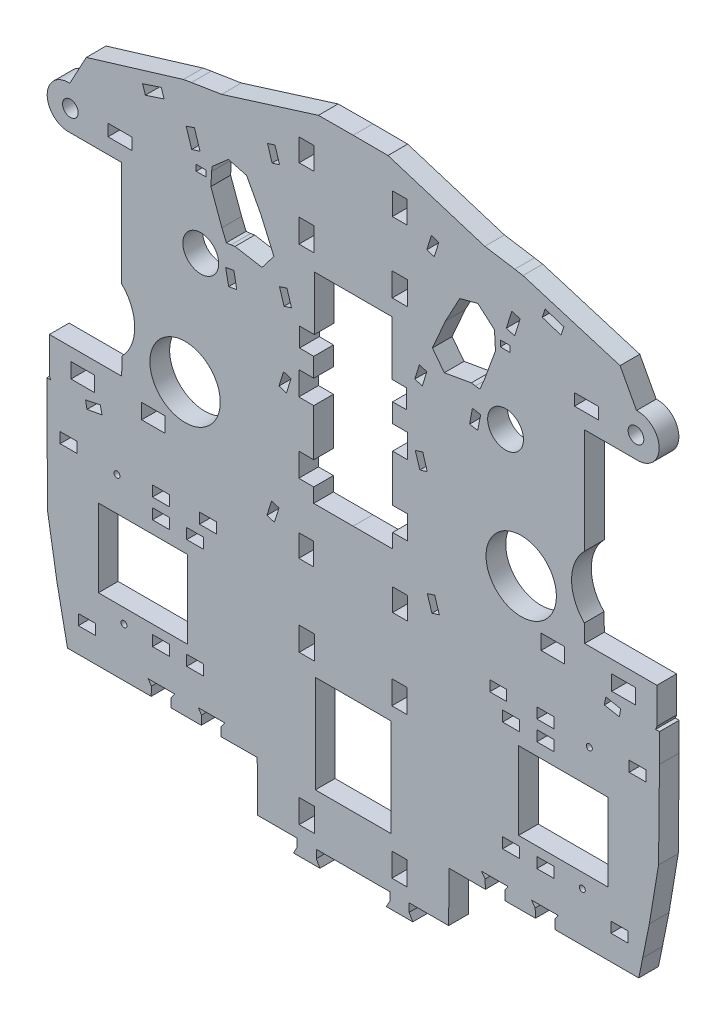
SolidWorks part; units mm, degrees
ref_plane "前视基准面" through (0, 0, 0) normal (0, 0, 1) x (1, 0, 0)
ref_plane "上视基准面" through (0, 0, 0) normal (0, 1, 0) x (1, 0, 0)
ref_plane "右视基准面" through (0, 0, 0) normal (1, 0, 0) x (0, 0, -1)
sketch "草图1" plane through (0, 0, 0) normal (0, 0, 1) x (1, 0, 0)
  line L0 (40.1319, 121.5955) -> (40.4636, 123.1274)
  line L1 (-23.8193, 113.4276) -> (-23.8217, 138.8533)
  line L2 (-75.4253, 72.6956) -> (-75.3783, 72.6832)
  line L3 (-75.4995, 72.7153) -> (-75.4253, 72.6956)
  line L4 (-64.2128, 53.4964) -> (-64.2329, 53.6251)
  line L5 (-69.9682, 79.3438) -> (-69.9274, 79.3967)
  line L6 (-43.5933, 134.7383) -> (-43.5944, 146.0263)
  line L7 (-71.2784, 60.0877) -> (-71.2024, 60.1943)
  line L8 (-76.5092, -117.3385) -> (-76.4093, -117.3385)
  line L9 (-79.6948, -128.8921) -> (-78.1517, -128.025)
  line L10 (-76.5083, -127.1017) -> (-76.4368, -127.1017)
  line L11 (-76.5136, -70.2234) -> (-76.4137, -70.2234)
  line L12 (-76.5127, -79.9866) -> (-76.4128, -79.9866)
  line L13 (-72.2367, -65.4) -> (-68.3488, -65.3726)
  line L14 (45.1325, -17.5397) -> (47.3975, -15.7128)
  line L15 (45.1036, -17.563) -> (45.1325, -17.5397)
  line L16 (21.5769, 33.5708) -> (25.2245, 34.8805)
  line L17 (22.1508, 30.3689) -> (21.5769, 33.5708)
  line L18 (-23.565, -53.6074) -> (-5.931, -53.5258)
  line L19 (46.0726, -27.5191) -> (48.4576, -28.9466)
  line L20 (-19.3181, -41.989) -> (-17.0621, -43.6655)
  line L21 (23.8684, 46.73) -> (23.9576, 46.855)
  line L22 (23.8388, 46.6886) -> (23.8684, 46.73)
  line L23 (27.9944, 34.276) -> (28.1788, 34.2274)
  line L24 (41.1158, -17.8347) -> (45.1036, -17.563)
  line L25 (-19.5903, -41.9817) -> (-19.3181, -41.989)
  line L26 (47.4028, -15.7672) -> (47.3975, -15.7128)
  line L27 (24.5751, -117.3132) -> (24.5716, -79.9772)
  line L28 (78.1472, 49.3388) -> (84.2446, 51.2521)
  line L29 (16.7435, 53.3987) -> (16.7367, 53.4443)
  line L30 (-96.1195, -29.1142) -> (-96.1023, -28.9384)
  line L31 (-69.0029, 33.531) -> (-68.9973, 33.5623)
  line L32 (-51.1518, -3.924) -> (-51.153, 8.006)
  line L33 (-75.5974, 34.2157) -> (-75.5862, 34.2494)
  line L34 (-94.8087, -15.7261) -> (-92.7022, -17.4264)
  line L35 (-93.4236, -27.4919) -> (-89.6822, -27.7541)
  line L36 (-64.3223, 53.462) -> (-64.3152, 53.5103)
  line L37 (-6.1906, 160.47) -> (42.9188, 145.1172)
  line L38 (47.1449, 122.6663) -> (44.8512, 124.5174)
  line L39 (44.8512, 124.5174) -> (40.8238, 124.7905)
  line L40 (-4.0345, 98.9639) -> (-4.0235, 110.8835)
  line L41 (30.217, 115.8395) -> (23.0051, 102.396)
  line L42 (3.6524, 110.864) -> (-4.0235, 110.8835)
  line L43 (17.3013, 127.7476) -> (13.5193, 128.917)
  line L44 (16.3574, 87.2049) -> (22.4022, 79.3476)
  line L45 (3.6414, 98.9339) -> (-4.0345, 98.9639)
  line L46 (-3.9865, 146.0307) -> (3.5762, 146.0856)
  line L47 (19.6115, 135.2186) -> (15.8418, 136.3843)
  line L48 (19.6115, 135.2186) -> (17.3013, 127.7476)
  line L49 (39.4156, 118.2877) -> (39.503, 118.6909)
  line L50 (13.5193, 128.917) -> (15.8418, 136.3843)
  line L51 (39.4156, 118.2877) -> (30.217, 115.8395)
  line L52 (16.3574, 87.2049) -> (23.0051, 102.396)
  line L53 (3.6414, 98.9339) -> (3.6524, 110.864)
  line L54 (3.5771, 134.7408) -> (3.5762, 146.0856)
  line L55 (21.9145, 62.6193) -> (18.2054, 63.9673)
  line L56 (-17.048, 115.4151) -> (-19.5729, 113.5388)
  line L57 (-6.1906, 160.47) -> (-23.8228, 160.5481)
  line L58 (-23.8163, 90.6556) -> (-4.1414, 90.6574)
  line L59 (11.2182, 67.904) -> (7.4362, 69.0735)
  line L60 (3.3412, 53.5022) -> (3.3403, 63.1315)
  line L61 (-19.5729, 113.5388) -> (-23.8193, 113.4276)
  line L62 (18.1801, 63.7969) -> (18.2054, 63.9673)
  line L63 (-17.0496, 137.3564) -> (-17.0513, 150.8079)
  line L64 (7.4362, 69.0735) -> (9.7596, 76.5405)
  line L65 (-17.0463, 101.9645) -> (-19.5098, 103.5819)
  line L66 (-3.9864, 134.7429) -> (3.5771, 134.7408)
  line L67 (-17.0463, 101.9645) -> (-17.048, 115.4151)
  line L68 (-23.8226, 148.8204) -> (-23.8228, 160.5481)
  line L69 (-4.1388, 63.1308) -> (-4.1414, 90.6574)
  line L70 (13.5284, 75.3751) -> (9.7596, 76.5405)
  line L71 (11.2182, 67.904) -> (13.5284, 75.3751)
  line L72 (3.3403, 63.1315) -> (-4.1388, 63.1308)
  line L73 (-63.9249, 87.1964) -> (-70.5783, 102.3878)
  line L74 (-50.9578, 53.4976) -> (-50.9587, 63.1256)
  line L75 (-50.9587, 63.1256) -> (-43.4827, 63.1263)
  line L76 (-43.4827, 63.1263) -> (-43.4852, 90.6543)
  line L77 (-65.7707, 63.9602) -> (-69.4786, 62.6119)
  line L78 (-90.4983, 145.1059) -> (-41.3917, 160.4665)
  line L79 (-51.214, 98.9296) -> (-43.534, 98.9623)
  line L80 (-70.5783, 102.3878) -> (-77.7916, 115.8311)
  line L81 (-41.3917, 160.4665) -> (-23.8228, 160.5481)
  line L82 (-43.4852, 90.6543) -> (-23.8163, 90.6556)
  line L83 (-94.7202, 122.6535) -> (-96.0334, 136.0414)
  line L84 (-93.3364, 134.4217) -> (-89.4053, 134.694)
  line L85 (-51.1544, 146.0816) -> (-51.1533, 134.7376)
  line L86 (-64.8767, 127.7403) -> (-61.0968, 128.9127)
  line L87 (-58.8382, 67.8971) -> (-61.1509, 75.3687)
  line L88 (-77.7916, 115.8311) -> (-86.9918, 118.2783)
  line L89 (-43.534, 98.9623) -> (-43.5471, 110.8823)
  line L90 (-89.4053, 134.694) -> (-90.4983, 145.1059)
  line L91 (-57.3799, 76.537) -> (-61.1509, 75.3687)
  line L92 (-51.1533, 134.7376) -> (-43.5933, 134.7383)
  line L93 (-61.0968, 128.9127) -> (-63.4215, 136.3764)
  line L94 (-57.3799, 76.537) -> (-55.0552, 69.0692)
  line L95 (-64.8767, 127.7403) -> (-67.1894, 135.2121)
  line L96 (-43.5944, 146.0263) -> (-51.1544, 146.0816)
  line L97 (-63.4215, 136.3764) -> (-67.1894, 135.2121)
  line L98 (-51.2271, 110.8576) -> (-51.214, 98.9296)
  line L99 (-43.5471, 110.8823) -> (-51.2271, 110.8576)
  line L100 (-58.8382, 67.8971) -> (-55.0552, 69.0692)
  line L101 (-72.7515, 71.9876) -> (-75.3783, 72.6832)
  line L102 (-71.2024, 60.1943) -> (-69.4786, 62.6119)
  line L103 (-64.0962, 53.4964) -> (-50.9578, 53.4976)
  line L104 (-19.5419, 138.9757) -> (-19.5131, 138.9747)
  line L105 (60.0533, -65.6151) -> (105.3501, -65.6151)
  line L106 (124.7675, -49.2798) -> (124.7675, -43.9386)
  line L107 (106.9126, -119.2515) -> (106.9126, -124.5927)
  line L108 (131.5142, -23.7313) -> (131.5142, -38.1518)
  line L109 (60.0533, -65.6151) -> (60.0533, -105.0597)
  line L110 (105.3501, -105.0597) -> (60.0533, -105.0597)
  line L111 (116.1591, -43.9386) -> (124.7675, -43.9386)
  line L112 (115.5201, -124.5927) -> (106.9126, -124.5927)
  line L113 (32.2419, -129.0028) -> (32.2419, -115.5769)
  line L114 (32.0238, -115.6974) -> (32.2419, -115.5769)
  line L115 (115.5201, -124.5927) -> (115.5201, -119.2515)
  line L116 (131.5142, -23.7313) -> (129.5469, -23.7313)
  line L117 (124.7675, -49.2798) -> (116.1601, -49.2798)
  line L118 (32.2419, -81.8877) -> (32.2419, -68.4618)
  line L119 (28.9553, -117.3934) -> (24.7931, -117.3934)
  line L120 (24.7931, -137.0741) -> (24.7931, -127.1566)
  line L121 (43.2128, -137.1757) -> (24.7931, -137.0741)
  line L122 (43.2128, -137.1757) -> (43.1019, -132.6787)
  line L123 (43.1019, -132.6787) -> (41.2259, -130.1536)
  line L124 (41.2259, -130.1536) -> (54.6773, -130.1531)
  line L125 (53.0588, -132.6165) -> (54.6773, -130.1531)
  line L126 (53.1798, -137.1757) -> (53.0588, -132.6165)
  line L127 (68.6037, -137.1757) -> (53.1798, -137.1757)
  line L128 (68.4928, -132.6787) -> (68.6037, -137.1757)
  line L129 (66.6168, -130.1536) -> (68.4928, -132.6787)
  line L130 (80.0682, -130.1531) -> (66.6168, -130.1536)
  line L131 (78.4498, -132.6165) -> (80.0682, -130.1531)
  line L132 (78.5707, -137.1757) -> (78.4498, -132.6165)
  line L133 (78.5707, -137.1757) -> (121.0052, -137.2023)
  line L134 (123.0125, -127.3697) -> (121.0052, -137.2023)
  line L135 (123.0125, -127.3697) -> (126.3749, -110.7223)
  line L136 (131.0458, -82.5131) -> (126.3749, -110.7223)
  line L137 (131.5142, -38.1518) -> (131.0458, -82.5131)
  line L138 (123.7326, -38.1518) -> (114.1111, -38.1518)
  line L139 (114.1111, -38.1518) -> (113.9902, -33.5926)
  line L140 (115.6087, -31.1292) -> (113.9902, -33.5926)
  line L141 (102.1572, -31.1297) -> (115.6087, -31.1292)
  line L142 (104.0332, -33.6548) -> (102.1572, -31.1297)
  line L143 (104.1441, -38.1518) -> (104.0332, -33.6548)
  line L144 (78.8927, -38.1518) -> (104.1441, -38.1518)
  line L145 (78.7718, -33.5926) -> (78.8927, -38.1518)
  line L146 (66.9388, -31.1297) -> (80.3894, -31.1332)
  line L147 (68.8148, -33.6548) -> (66.9388, -31.1297)
  line L148 (68.9257, -38.1518) -> (68.8148, -33.6548)
  line L149 (28.9553, -70.2783) -> (24.7931, -70.2783)
  line L150 (91.7893, -110.9056) -> (92.3726, -110.7896)
  line L151 (92.9558, -110.9056) -> (92.3726, -110.7896)
  line L152 (93.4502, -111.236) -> (92.9558, -110.9056)
  line L153 (93.7806, -111.7304) -> (93.4502, -111.236)
  line L154 (93.8966, -112.3136) -> (93.7806, -111.7304)
  line L155 (93.7806, -112.8969) -> (93.8966, -112.3136)
  line L156 (93.4502, -113.3913) -> (93.7806, -112.8969)
  line L157 (92.9558, -113.7217) -> (93.4502, -113.3913)
  line L158 (92.3726, -113.8377) -> (92.9558, -113.7217)
  line L159 (91.7893, -113.7217) -> (92.3726, -113.8377)
  line L160 (91.2949, -113.3913) -> (91.7893, -113.7217)
  line L161 (90.9645, -112.8969) -> (91.2949, -113.3913)
  line L162 (90.8485, -112.3136) -> (90.9645, -112.8969)
  line L163 (90.9645, -111.7304) -> (90.8485, -112.3136)
  line L164 (91.2949, -111.236) -> (90.9645, -111.7304)
  line L165 (91.7893, -110.9056) -> (91.2949, -111.236)
  line L166 (116.1591, -43.9386) -> (116.1601, -49.2798)
  line L167 (106.9126, -119.2515) -> (115.5201, -119.2515)
  line L168 (94.5362, -48.9646) -> (94.8665, -49.459)
  line L169 (94.4202, -48.3814) -> (94.5362, -48.9646)
  line L170 (94.5362, -47.7982) -> (94.4202, -48.3814)
  line L171 (94.8665, -47.3037) -> (94.5362, -47.7982)
  line L172 (95.361, -46.9734) -> (94.8665, -47.3037)
  line L173 (95.361, -46.9734) -> (95.9442, -46.8574)
  line L174 (95.9442, -46.8574) -> (96.5274, -46.9734)
  line L175 (96.5274, -46.9734) -> (97.0218, -47.3037)
  line L176 (97.0218, -47.3037) -> (97.3522, -47.7982)
  line L177 (97.4682, -48.3814) -> (97.3522, -47.7982)
  line L178 (97.3522, -48.9646) -> (97.4682, -48.3814)
  line L179 (97.3522, -48.9646) -> (97.0218, -49.459)
  line L180 (97.0218, -49.459) -> (96.5274, -49.7894)
  line L181 (96.5274, -49.7894) -> (95.9442, -49.9054)
  line L182 (95.9442, -49.9054) -> (95.361, -49.7894)
  line L183 (95.361, -49.7894) -> (94.8665, -49.459)
  line L184 (77.9262, -49.2798) -> (77.9262, -43.9386)
  line L185 (77.9262, -49.2798) -> (69.3177, -49.2798)
  line L186 (69.3177, -49.2798) -> (69.3177, -43.9386)
  line L187 (69.3177, -43.9386) -> (77.9262, -43.9386)
  line L188 (54.053, -43.9386) -> (54.053, -49.2798)
  line L189 (45.4446, -49.2798) -> (54.053, -49.2798)
  line L190 (45.4446, -49.2798) -> (45.4446, -43.9386)
  line L191 (45.4446, -43.9386) -> (54.053, -43.9386)
  line L192 (60.5583, -53.9613) -> (60.5583, -59.3025)
  line L193 (51.9499, -59.3025) -> (60.5583, -59.3025)
  line L194 (51.9499, -53.9613) -> (51.9499, -59.3025)
  line L195 (51.9499, -53.9613) -> (60.5583, -53.9613)
  line L196 (77.9262, -59.3025) -> (69.3177, -59.3025)
  line L197 (69.3177, -53.9613) -> (69.3177, -59.3025)
  line L198 (69.3177, -53.9613) -> (77.9262, -53.9613)
  line L199 (51.9513, -114.9842) -> (60.5597, -114.9842)
  line L200 (51.9513, -109.643) -> (51.9513, -114.9842)
  line L201 (60.5597, -109.643) -> (51.9513, -109.643)
  line L202 (60.5597, -114.9842) -> (60.5597, -109.643)
  line L203 (77.9262, -114.9842) -> (77.9262, -109.643)
  line L204 (69.3177, -114.9842) -> (77.9262, -114.9842)
  line L205 (69.3177, -109.643) -> (69.3177, -114.9842)
  line L206 (77.9262, -109.643) -> (69.3177, -109.643)
  line L207 (105.3501, -65.6151) -> (105.3501, -105.0597)
  line L208 (28.849, -80.0414) -> (24.7931, -80.0612)
  line L209 (32.2419, -81.8877) -> (32.0007, -81.7522)
  line L210 (32.0194, -68.5847) -> (32.2419, -68.4618)
  line L211 (28.8818, -127.1566) -> (24.7931, -127.1566)
  line L212 (77.9271, -59.2742) -> (77.9262, -59.3025)
  line L213 (-152.9089, -65.5674) -> (-107.6121, -65.5631)
  line L214 (-172.3284, -43.8927) -> (-172.3279, -49.2339)
  line L215 (-154.4655, -119.2039) -> (-154.465, -124.5451)
  line L216 (-179.076, -23.686) -> (-179.0746, -38.1065)
  line L217 (-107.6084, -105.0078) -> (-107.6121, -65.5631)
  line L218 (-107.6084, -105.0078) -> (-152.9052, -105.012)
  line L219 (-172.3284, -43.8927) -> (-163.72, -43.8919)
  line L220 (-163.0734, -124.5459) -> (-154.465, -124.5451)
  line L221 (-79.7939, -128.9477) -> (-79.7951, -115.5227)
  line L222 (-163.0734, -124.5459) -> (-163.0739, -119.2047)
  line L223 (-179.076, -23.686) -> (-177.1096, -23.6858)
  line L224 (-172.3279, -49.2339) -> (-163.7195, -49.233)
  line L225 (-79.7983, -81.8326) -> (-79.7995, -68.4076)
  line L226 (-72.3461, -117.3222) -> (-72.3496, -80.006)
  line L227 (-72.3443, -137.0189) -> (-72.3452, -127.1014)
  line L228 (-90.764, -137.1222) -> (-72.3443, -137.0189)
  line L229 (-88.7787, -130.0999) -> (-102.2292, -130.1007)
  line L230 (-100.6105, -132.5639) -> (-102.2292, -130.1007)
  line L231 (-100.731, -137.1231) -> (-100.6105, -132.5639)
  line L232 (-116.1549, -137.1246) -> (-100.731, -137.1231)
  line L233 (-127.6201, -130.1031) -> (-114.1696, -130.1023)
  line L234 (-126.0014, -132.5663) -> (-127.6201, -130.1031)
  line L235 (-126.1219, -137.1255) -> (-126.0014, -132.5663)
  line L236 (-64.3466, -46.4962) -> (-89.1328, -38.6309)
  line L237 (-90.582, -38.1713) -> (-90.7877, -38.1058)
  line L238 (-64.3449, -65.3254) -> (-64.3466, -46.4962)
  line L239 (-72.3509, -65.4009) -> (-72.2367, -65.4)
  line L240 (-72.3505, -70.223) -> (-72.3509, -65.4009)
  line L241 (-140.5094, -110.8568) -> (-139.9267, -110.7408)
  line L242 (-141.0038, -111.1872) -> (-140.5094, -110.8568)
  line L243 (-141.3341, -111.6816) -> (-141.0038, -111.1872)
  line L244 (-141.4501, -112.2649) -> (-141.3341, -111.6816)
  line L245 (-141.334, -112.8481) -> (-141.4501, -112.2649)
  line L246 (-141.0036, -113.3425) -> (-141.334, -112.8481)
  line L247 (-140.5092, -113.6728) -> (-141.0036, -113.3425)
  line L248 (-139.9264, -113.7887) -> (-140.5092, -113.6728)
  line L249 (-143.5043, -46.8089) -> (-144.087, -46.9249)
  line L250 (-144.087, -46.9249) -> (-144.5814, -47.2552)
  line L251 (-144.5814, -47.2552) -> (-144.9117, -47.7497)
  line L252 (-145.0277, -48.3329) -> (-144.9117, -47.7497)
  line L253 (-144.9116, -48.9162) -> (-145.0277, -48.3329)
  line L254 (-144.9116, -48.9162) -> (-144.5812, -49.4106)
  line L255 (-144.5812, -49.4106) -> (-144.0868, -49.7409)
  line L256 (-144.0868, -49.7409) -> (-143.504, -49.8567)
  line L257 (-125.4856, -49.2295) -> (-125.4861, -43.8883)
  line L258 (-101.6129, -43.8861) -> (-101.6124, -49.2273)
  line L259 (-93.0049, -49.2265) -> (-101.6124, -49.2273)
  line L260 (-108.1173, -53.9094) -> (-108.1168, -59.2506)
  line L261 (-99.5093, -59.2498) -> (-108.1168, -59.2506)
  line L262 (-125.4851, -53.911) -> (-125.4846, -59.2522)
  line L263 (-99.5055, -114.9316) -> (-108.113, -114.9324)
  line L264 (-108.1135, -109.5912) -> (-99.506, -109.5903)
  line L265 (-108.113, -114.9324) -> (-108.1135, -109.5912)
  line L266 (-125.4794, -114.934) -> (-125.4799, -109.5928)
  line L267 (-116.872, -114.9332) -> (-125.4794, -114.934)
  line L268 (-125.4799, -109.5928) -> (-116.8725, -109.592)
  line L269 (-152.9089, -65.5674) -> (-152.9052, -105.012)
  line L270 (-127.9521, -31.0791) -> (-114.5008, -31.0783)
  line L271 (-126.4538, -38.1016) -> (-126.3333, -33.5425)
  line L272 (-151.7055, -38.1039) -> (-126.4538, -38.1016)
  line L273 (-163.1705, -31.0824) -> (-149.7192, -31.0815)
  line L274 (-161.5517, -33.5457) -> (-163.1705, -31.0824)
  line L275 (-161.6722, -38.1049) -> (-161.5517, -33.5457)
  line L276 (-161.6722, -38.1049) -> (-171.294, -38.1058)
  line L277 (-178.6031, -82.4678) -> (-179.0746, -38.1065)
  line L278 (-173.9295, -110.6765) -> (-178.6031, -82.4678)
  line L279 (-170.5656, -127.3237) -> (-173.9295, -110.6765)
  line L280 (-168.5574, -137.156) -> (-170.5656, -127.3237)
  line L281 (-126.1219, -137.1255) -> (-168.5574, -137.156)
  line L282 (-116.0453, -132.6276) -> (-114.1696, -130.1023)
  line L283 (-116.1549, -137.1246) -> (-116.0453, -132.6276)
  line L284 (-90.6544, -132.6252) -> (-88.7787, -130.0999)
  line L285 (-90.764, -137.1222) -> (-90.6544, -132.6252)
  line L286 (-139.3439, -110.8567) -> (-139.9267, -110.7408)
  line L287 (-138.8495, -111.187) -> (-139.3439, -110.8567)
  line L288 (-138.5191, -111.6814) -> (-138.8495, -111.187)
  line L289 (-138.403, -112.2646) -> (-138.5191, -111.6814)
  line L290 (-138.5189, -112.8478) -> (-138.403, -112.2646)
  line L291 (-138.8493, -113.3423) -> (-138.5189, -112.8478)
  line L292 (-139.3437, -113.6727) -> (-138.8493, -113.3423)
  line L293 (-139.9264, -113.7887) -> (-139.3437, -113.6727)
  line L294 (-116.872, -114.9332) -> (-116.8725, -109.592)
  line L295 (-125.4856, -49.2295) -> (-116.8781, -49.2287)
  line L296 (-125.4861, -43.8883) -> (-116.8786, -43.8875)
  line L297 (-116.8786, -43.8875) -> (-116.8781, -49.2287)
  line L298 (-93.0054, -43.8853) -> (-101.6129, -43.8861)
  line L299 (-93.0049, -49.2265) -> (-93.0054, -43.8853)
  line L300 (-108.1173, -53.9094) -> (-99.5098, -53.9086)
  line L301 (-99.5093, -59.2498) -> (-99.5098, -53.9086)
  line L302 (-163.7195, -49.233) -> (-163.72, -43.8919)
  line L303 (-125.4846, -59.2522) -> (-116.8772, -59.2514)
  line L304 (-125.4851, -53.911) -> (-116.8777, -53.9102)
  line L305 (-116.8772, -59.2514) -> (-116.8777, -53.9102)
  line L306 (-143.504, -49.8567) -> (-142.9213, -49.7408)
  line L307 (-143.5043, -46.8089) -> (-142.9215, -46.9247)
  line L308 (-142.4271, -47.255) -> (-142.9215, -46.9247)
  line L309 (-142.0966, -47.7494) -> (-142.4271, -47.255)
  line L310 (-141.9806, -48.3327) -> (-142.0966, -47.7494)
  line L311 (-142.0965, -48.9159) -> (-141.9806, -48.3327)
  line L312 (-142.4269, -49.4104) -> (-142.0965, -48.9159)
  line L313 (-142.9213, -49.7408) -> (-142.4269, -49.4104)
  line L314 (-163.0739, -119.2047) -> (-154.4655, -119.2039)
  line L315 (-99.5055, -114.9316) -> (-99.506, -109.5903)
  line L316 (3.7406, -27.7949) -> (-3.8354, -27.7976)
  line L317 (-16.7939, -43.8648) -> (-16.7952, -30.4148)
  line L318 (3.735, 31.8031) -> (3.7339, 43.8151)
  line L319 (-3.841, 31.8024) -> (3.735, 31.8031)
  line L320 (-3.841, 31.8024) -> (-3.8388, 7.9804)
  line L321 (3.7372, 8.0131) -> (-3.8388, 7.9804)
  line L322 (3.7383, -3.9169) -> (3.7372, 8.0131)
  line L323 (-3.8376, -3.9396) -> (3.7383, -3.9169)
  line L324 (-3.837, -11.1616) -> (-3.8376, -3.9396)
  line L325 (-23.569, -11.1894) -> (-3.837, -11.1616)
  line L326 (-23.567, -31.9134) -> (-23.569, -11.1894)
  line L327 (23.2536, 4.5529) -> (30.4688, -8.8884)
  line L328 (22.6474, 27.5989) -> (16.6041, 19.7443)
  line L329 (-3.8421, 43.8144) -> (-3.843, 53.4364)
  line L330 (3.7339, 43.8151) -> (-3.8421, 43.8144)
  line L331 (-3.8354, -27.7976) -> (-3.8344, -39.0856)
  line L332 (3.7416, -39.1389) -> (3.7406, -27.7949)
  line L333 (-3.8344, -39.0856) -> (3.7416, -39.1389)
  line L334 (17.5539, -20.7996) -> (13.772, -21.9699)
  line L335 (17.5539, -20.7996) -> (19.8666, -28.2694)
  line L336 (16.0967, -29.4357) -> (19.8666, -28.2694)
  line L337 (13.772, -21.9699) -> (16.0967, -29.4357)
  line L338 (7.6785, 37.8735) -> (10.0031, 30.4057)
  line L339 (11.4603, 39.0438) -> (7.6785, 37.8735)
  line L340 (13.771, 31.5721) -> (11.4603, 39.0438)
  line L341 (10.0031, 30.4057) -> (13.771, 31.5721)
  line L342 (25.3725, 34.9333) -> (25.4267, 34.9531)
  line L343 (22.6474, 27.5989) -> (22.1508, 30.3689)
  line L344 (16.5011, 53.4442) -> (-3.843, 53.4364)
  line L345 (-17.0634, -30.5911) -> (-16.7952, -30.4148)
  line L346 (-16.7939, -43.8648) -> (-17.0621, -43.6655)
  line L347 (48.7107, -29.0987) -> (47.4028, -15.7672)
  line L348 (18.446, 42.9805) -> (18.421, 43.1493)
  line L349 (-54.121, -169.8559) -> (-52.2752, -166.569)
  line L350 (-72.2428, -162.4166) -> (-72.2461, -127.0854)
  line L351 (-51.2429, -155.9829) -> (-43.5661, -156.0025)
  line L352 (-43.5731, -80.2888) -> (-43.5622, -68.3693)
  line L353 (16.787, -65.3179) -> (16.5691, -65.3179)
  line L354 (-72.2514, -70.223) -> (-72.3505, -70.223)
  line L355 (16.5691, -65.3179) -> (16.5674, -46.4874)
  line L356 (-64.2498, -65.3254) -> (-64.2516, -46.4422)
  line L357 (-54.121, -169.8559) -> (-40.6941, -169.8546)
  line L358 (-40.6941, -169.8546) -> (-42.511, -166.5681)
  line L359 (24.5716, -79.9772) -> (28.7339, -79.9768)
  line L360 (-76.4368, -127.1017) -> (-76.4084, -127.0858)
  line L361 (-72.3496, -80.006) -> (-72.2505, -79.9862)
  line L362 (-76.4128, -79.9866) -> (-79.6992, -81.8331)
  line L363 (-42.511, -166.5681) -> (-42.5114, -162.4099)
  line L364 (-6.7803, -162.4066) -> (-5.1763, -162.4064)
  line L365 (24.7931, -70.214) -> (24.5716, -70.214)
  line L366 (-72.247, -117.3222) -> (-72.3461, -117.3222)
  line L367 (-50.3074, -50.7676) -> (-64.2516, -46.4422)
  line L368 (-23.565, -53.375) -> (-23.8392, -53.3751)
  line L369 (-5.1759, -166.5646) -> (-5.1763, -162.4064)
  line L370 (-7.0219, -169.8515) -> (-5.1759, -166.5646)
  line L371 (-79.7005, -68.407) -> (-76.4137, -70.2234)
  line L372 (32.0113, -128.8733) -> (32.0238, -115.6974)
  line L373 (3.5339, -155.9779) -> (-4.2194, -155.9777)
  line L374 (24.577, -127.0764) -> (28.7382, -127.076)
  line L375 (24.7931, -117.3132) -> (24.5751, -117.3132)
  line L376 (-43.5661, -156.0025) -> (-43.5551, -144.0828)
  line L377 (-39.3234, -162.4135) -> (-8.3843, -162.4107)
  line L378 (-42.5114, -162.4099) -> (-40.9055, -162.4097)
  line L379 (3.5268, -144.0477) -> (-4.1562, -144.0792)
  line L380 (32.0007, -81.7522) -> (32.0194, -68.5847)
  line L381 (-51.2389, -68.3392) -> (-51.25, -80.2693)
  line L382 (3.5268, -80.2642) -> (-4.2265, -80.2641)
  line L383 (-72.247, -117.3222) -> (-72.2505, -79.9862)
  line L384 (28.7329, -70.2136) -> (32.0194, -68.3968)
  line L385 (28.7373, -117.3128) -> (32.0238, -115.496)
  line L386 (-43.5551, -144.0828) -> (-51.2319, -144.0528)
  line L387 (-51.25, -80.2693) -> (-43.5731, -80.2888)
  line L388 (-5.7866, -53.3734) -> (16.5664, -46.4347)
  line L389 (-51.2319, -144.0528) -> (-51.2429, -155.9829)
  line L390 (-52.2752, -166.569) -> (-52.2755, -162.4107)
  line L391 (-43.5622, -68.3693) -> (-51.2389, -68.3392)
  line L392 (-4.2265, -80.2641) -> (-4.1623, -68.3656)
  line L393 (24.5793, -162.4076) -> (24.577, -127.0764)
  line L394 (-4.2194, -155.9777) -> (-4.1562, -144.0792)
  line L395 (3.5268, -80.2642) -> (3.5137, -68.3341)
  line L396 (4.5882, -166.5637) -> (4.5869, -162.4015)
  line L397 (6.4052, -169.8502) -> (4.5882, -166.5637)
  line L398 (-7.0219, -169.8515) -> (6.4052, -169.8502)
  line L399 (-64.2498, -65.3254) -> (-64.3449, -65.3254)
  line L400 (24.5716, -70.214) -> (24.5703, -65.4547)
  line L401 (-4.1623, -68.3656) -> (3.5137, -68.3341)
  line L402 (-42.9186, -136.5506) -> (-42.8629, -87.0104)
  line L403 (-4.7404, -136.631) -> (-42.9186, -136.5506)
  line L404 (-4.6848, -87.1346) -> (-42.8629, -87.0104)
  line L405 (-79.6961, -115.5062) -> (-76.4093, -117.3385)
  line L406 (-4.7404, -136.631) -> (-4.6848, -87.1346)
  line L407 (16.6681, 19.725) -> (23.205, 4.723)
  line L408 (130.2103, -4.0184) -> (93.5623, -4.0218)
  line L409 (78.8988, 13.0077) -> (79.2419, 9.5268)
  line L410 (76.2339, 19.4395) -> (77.883, 16.3548)
  line L411 (76.2358, -0.3865) -> (74.017, -3.0906)
  line L412 (80.3678, 57.3955) -> (81.8198, 53.1379)
  line L413 (93.5411, 61.5734) -> (93.5484, 36.5375)
  line L414 (86.8457, 20.7302) -> (87.2756, 16.3691)
  line L415 (43.9002, 6.0425) -> (44.9158, 2.6954)
  line L416 (46.0726, -27.5191) -> (42.116, -27.7881)
  line L417 (90.611, 33.1498) -> (93.5484, 36.5375)
  line L418 (88.5456, 29.2849) -> (90.611, 33.1498)
  line L419 (81.8198, 53.1379) -> (84.3658, 51.2901)
  line L420 (90.6142, 8.3112) -> (93.3945, 4.924)
  line L421 (79.2419, 9.5268) -> (78.8994, 6.0458)
  line L422 (44.9158, 2.6954) -> (46.565, -0.3892)
  line L423 (64.8784, 27.0255) -> (68.2256, 26.0105)
  line L424 (68.2256, 26.0105) -> (71.3106, 24.3619)
  line L425 (130.213, -22.0723) -> (130.2103, -4.0184)
  line L426 (44.9137, 16.3518) -> (46.5622, 19.4367)
  line L427 (43.8986, 13.0045) -> (44.9137, 16.3518)
  line L428 (43.5561, 9.5235) -> (43.8986, 13.0045)
  line L429 (43.9002, 6.0425) -> (43.5561, 9.5235)
  line L430 (48.7833, -3.0929) -> (46.565, -0.3892)
  line L431 (51.4873, -5.3116) -> (48.7833, -3.0929)
  line L432 (54.5723, -6.9602) -> (51.4873, -5.3116)
  line L433 (57.9196, -7.9753) -> (54.5723, -6.9602)
  line L434 (61.4007, -8.3178) -> (57.9196, -7.9753)
  line L435 (64.8816, -7.9746) -> (61.4007, -8.3178)
  line L436 (68.2287, -6.959) -> (64.8816, -7.9746)
  line L437 (71.3133, -5.3098) -> (68.2287, -6.959)
  line L438 (74.017, -3.0906) -> (71.3133, -5.3098)
  line L439 (77.8843, 2.6985) -> (76.2358, -0.3865)
  line L440 (78.8994, 6.0458) -> (77.8843, 2.6985)
  line L441 (42.116, -27.7881) -> (43.2272, -38.1593)
  line L442 (47.4322, -15.7436) -> (48.7384, -29.1177)
  line L443 (41.1158, -17.8347) -> (45.1282, -17.5915)
  line L444 (39.7064, -11.3609) -> (41.1158, -17.8347)
  line L445 (22.788, 27.638) -> (16.6681, 19.725)
  line L446 (21.401, 33.5825) -> (25.2529, 34.9651)
  line L447 (23.7689, 46.8973) -> (21.9902, 44.4136)
  line L448 (74.0147, 22.1432) -> (76.2339, 19.4395)
  line L449 (71.3106, 24.3619) -> (74.0147, 22.1432)
  line L450 (61.3973, 27.368) -> (64.8784, 27.0255)
  line L451 (57.9164, 27.0249) -> (61.3973, 27.368)
  line L452 (54.5693, 26.0092) -> (57.9164, 27.0249)
  line L453 (51.4846, 24.3601) -> (54.5693, 26.0092)
  line L454 (48.7809, 22.1408) -> (51.4846, 24.3601)
  line L455 (46.5622, 19.4367) -> (48.7809, 22.1408)
  line L456 (71.4698, -18.1114) -> (71.4893, -10.4346)
  line L457 (83.3894, -18.1224) -> (71.4698, -18.1114)
  line L458 (83.4194, -10.4456) -> (83.3894, -18.1224)
  line L459 (71.4893, -10.4346) -> (83.4194, -10.4456)
  line L460 (119.235, -18.1191) -> (107.3154, -18.1081)
  line L461 (119.265, -10.4423) -> (119.235, -18.1191)
  line L462 (107.3349, -10.4312) -> (119.265, -10.4423)
  line L463 (107.3154, -18.1081) -> (107.3349, -10.4312)
  line L464 (111.8505, -23.5622) -> (111.1537, -27.3996)
  line L465 (104.3599, -22.0472) -> (111.8505, -23.5622)
  line L466 (103.5368, -26.0134) -> (104.3599, -22.0472)
  line L467 (111.1537, -27.3996) -> (103.5368, -26.0134)
  line L468 (47.4322, -15.7436) -> (47.4028, -15.7672)
  line L469 (21.9902, 44.4136) -> (18.421, 43.1493)
  line L470 (88.5456, 29.2849) -> (87.2748, 25.0912)
  line L471 (87.2756, 16.3691) -> (88.5481, 12.1757)
  line L472 (87.2748, 25.0912) -> (86.8457, 20.7302)
  line L473 (88.5481, 12.1757) -> (90.6142, 8.3112)
  line L474 (93.5623, -4.0218) -> (93.3945, 4.924)
  line L475 (-92.3865, -17.5865) -> (-92.5136, -17.5779)
  line L476 (-88.4865, -17.8495) -> (-87.0791, -11.3473)
  line L477 (-64.9634, -20.8076) -> (-67.2726, -28.2775)
  line L478 (-90.582, -38.1713) -> (-89.4896, -27.7676)
  line L479 (-92.5136, -17.5779) -> (-92.5611, -17.5395)
  line L480 (-43.5706, -39.0913) -> (-43.5716, -27.8033)
  line L481 (-43.5716, -27.8033) -> (-51.1496, -27.8)
  line L482 (-64.3152, 53.4368) -> (-43.5792, 53.4327)
  line L483 (-69.5774, 44.3203) -> (-71.3776, 46.8461)
  line L484 (-70.6686, 4.5442) -> (-64.02, 19.7348)
  line L485 (-51.1518, -3.924) -> (-43.5738, -3.9433)
  line L486 (-64.02, 19.7348) -> (-70.0668, 27.5902)
  line L487 (-43.575, 7.9767) -> (-51.153, 8.006)
  line L488 (-61.1822, -21.9769) -> (-64.9634, -20.8076)
  line L489 (-63.5054, -29.4429) -> (-67.2726, -28.2775)
  line L490 (-51.1496, -27.8) -> (-51.1486, -39.146)
  line L491 (-69.5774, 44.3203) -> (-65.8682, 42.9726)
  line L492 (-87.0791, -11.3473) -> (-77.8794, -8.8985)
  line L493 (-63.5054, -29.4429) -> (-61.1822, -21.9769)
  line L494 (-43.5706, -39.0913) -> (-51.1486, -39.146)
  line L495 (-77.8794, -8.8985) -> (-70.6686, 4.5442)
  line L496 (-43.5783, 43.8087) -> (-51.1563, 43.808)
  line L497 (-51.1552, 31.798) -> (-43.5772, 31.7987)
  line L498 (-43.5738, -3.9433) -> (-43.5732, -11.1673)
  line L499 (-55.0977, 37.8676) -> (-58.8818, 39.0373)
  line L500 (-57.421, 30.3997) -> (-61.1902, 31.5651)
  line L501 (-43.575, 7.9767) -> (-43.5772, 31.7987)
  line L502 (-23.8403, -41.8795) -> (-23.5661, -41.8794)
  line L503 (-43.5792, 53.4327) -> (-43.5783, 43.8087)
  line L504 (-51.1563, 43.808) -> (-51.1552, 31.798)
  line L505 (-61.1902, 31.5651) -> (-58.8818, 39.0373)
  line L506 (-23.8422, -11.1895) -> (-43.5732, -11.1673)
  line L507 (-57.421, 30.3997) -> (-55.0977, 37.8676)
  line L508 (-19.6532, -32.0331) -> (-17.0634, -30.4148)
  line L509 (-17.0621, -43.6655) -> (-17.0634, -30.5911)
  line L510 (-23.8392, -53.6075) -> (-41.4732, -53.5291)
  line L511 (-23.8392, -53.3751) -> (-23.8403, -41.8795)
  line L512 (-23.8412, -31.9135) -> (-23.8422, -11.1895)
  line L513 (-17.0621, -43.8668) -> (-19.5903, -41.9817)
  line L514 (-131.9439, 51.3435) -> (-131.8406, 51.3115)
  line L515 (-119.1088, 47.3187) -> (-119.9162, 50.1536)
  line L516 (-64.2403, 19.791) -> (-70.7744, 4.7878)
  line L517 (-141.1301, -3.9702) -> (-177.7771, -3.9736)
  line L518 (-75.5834, 34.2976) -> (-72.8279, 35.0294)
  line L519 (-126.8113, 9.5811) -> (-126.4687, 13.0621)
  line L520 (-125.4537, 16.4094) -> (-123.8051, 19.4944)
  line L521 (-119.9162, 50.1536) -> (-118.4368, 54.4677)
  line L522 (-121.584, -3.0353) -> (-123.8033, -0.3316)
  line L523 (-127.947, 57.4495) -> (-129.3982, 53.1918)
  line L524 (-141.1228, 36.5892) -> (-141.1362, 61.6299)
  line L525 (-97.4406, 47.8963) -> (-91.5033, 49.2302)
  line L526 (-133.9369, 59.3276) -> (-141.1362, 61.6299)
  line L527 (-134.8462, 16.4219) -> (-134.4171, 20.783)
  line L528 (-92.4839, 2.7561) -> (-91.4689, 6.1034)
  line L529 (-70.3608, 27.7028) -> (-69.0029, 33.531)
  line L530 (-138.1856, 33.202) -> (-141.1228, 36.5892)
  line L531 (-136.1196, 29.3374) -> (-138.1856, 33.202)
  line L532 (-129.3982, 53.1918) -> (-131.9439, 51.3435)
  line L533 (-140.963, 4.9756) -> (-138.1833, 8.3634)
  line L534 (-126.4687, 13.0621) -> (-125.4537, 16.4094)
  line L535 (-126.4681, 6.1001) -> (-126.8113, 9.5811)
  line L536 (-94.1325, -0.3288) -> (-92.4839, 2.7561)
  line L537 (-115.798, 26.0668) -> (-112.451, 27.0825)
  line L538 (-118.8827, 24.4177) -> (-115.798, 26.0668)
  line L539 (-177.7771, -3.9736) -> (-177.7764, -22.0275)
  line L540 (-92.4852, 16.4125) -> (-94.1343, 19.4971)
  line L541 (-91.4695, 13.0654) -> (-92.4852, 16.4125)
  line L542 (-91.1263, 9.5845) -> (-91.4695, 13.0654)
  line L543 (-91.4689, 6.1034) -> (-91.1263, 9.5845)
  line L544 (-96.3512, -3.0329) -> (-94.1325, -0.3288)
  line L545 (-99.0548, -5.2522) -> (-96.3512, -3.0329)
  line L546 (-102.1395, -6.9013) -> (-99.0548, -5.2522)
  line L547 (-105.4866, -7.917) -> (-102.1395, -6.9013)
  line L548 (-108.9676, -8.2602) -> (-105.4866, -7.917)
  line L549 (-112.4486, -7.9177) -> (-108.9676, -8.2602)
  line L550 (-115.7959, -6.9026) -> (-112.4486, -7.9177)
  line L551 (-118.8809, -5.254) -> (-115.7959, -6.9026)
  line L552 (-121.584, -3.0353) -> (-118.8809, -5.254)
  line L553 (-125.4533, 2.753) -> (-123.8033, -0.3316)
  line L554 (-126.4681, 6.1001) -> (-125.4533, 2.753)
  line L555 (-94.9977, -15.6834) -> (-96.3015, -29.0578)
  line L556 (-87.2727, -11.2992) -> (-88.6767, -17.7959)
  line L557 (-78.0587, -8.8399) -> (-87.2727, -11.2992)
  line L558 (-70.7744, 4.7878) -> (-78.0587, -8.8399)
  line L559 (-70.3608, 27.7028) -> (-64.2403, 19.791)
  line L560 (-68.9758, 33.6476) -> (-72.8279, 35.0294)
  line L561 (-71.3462, 46.962) -> (-69.567, 44.4786)
  line L562 (-65.8442, 43.1607) -> (-69.567, 44.4786)
  line L563 (-121.5873, 22.1984) -> (-123.8051, 19.4944)
  line L564 (-118.8827, 24.4177) -> (-121.5873, 22.1984)
  line L565 (-108.9709, 27.4257) -> (-112.451, 27.0825)
  line L566 (-105.49, 27.0831) -> (-108.9709, 27.4257)
  line L567 (-102.1426, 26.0681) -> (-105.49, 27.0831)
  line L568 (-99.0577, 24.4195) -> (-102.1426, 26.0681)
  line L569 (-96.3536, 22.2008) -> (-99.0577, 24.4195)
  line L570 (-94.1343, 19.4971) -> (-96.3536, 22.2008)
  line L571 (-119.0349, -18.0557) -> (-119.0558, -10.3788)
  line L572 (-130.9545, -18.0689) -> (-119.0349, -18.0557)
  line L573 (-130.9859, -10.3921) -> (-130.9545, -18.0689)
  line L574 (-119.0558, -10.3788) -> (-130.9859, -10.3921)
  line L575 (-166.8001, -18.0722) -> (-154.8805, -18.059)
  line L576 (-166.8315, -10.3954) -> (-166.8001, -18.0722)
  line L577 (-154.9014, -10.3822) -> (-166.8315, -10.3954)
  line L578 (-154.8805, -18.059) -> (-154.9014, -10.3822)
  line L579 (-159.4146, -23.514) -> (-158.7171, -27.3513)
  line L580 (-151.9243, -21.9976) -> (-159.4146, -23.514)
  line L581 (-151.1004, -25.9636) -> (-151.9243, -21.9976)
  line L582 (-158.7171, -27.3513) -> (-151.1004, -25.9636)
  line L583 (-134.8471, 25.1441) -> (-136.1196, 29.3374)
  line L584 (-136.1179, 12.2283) -> (-134.8462, 16.4219)
  line L585 (-134.4171, 20.783) -> (-134.8471, 25.1441)
  line L586 (-138.1833, 8.3634) -> (-136.1179, 12.2283)
  line L587 (-90.7877, -38.1058) -> (-89.6822, -27.7541)
  line L588 (-65.8442, 43.1607) -> (-64.3223, 53.462)
  line L589 (-141.1301, -3.9702) -> (-140.963, 4.9756)
  line L590 (-136.0131, 103.6834) -> (-136.0131, 97.7273)
  line L591 (-136.0131, 103.6834) -> (-148.0991, 103.6834)
  line L592 (-136.0131, 97.7273) -> (-148.0991, 97.7273)
  line L593 (-148.0991, 103.6834) -> (-148.0991, 97.7273)
  line L594 (-170.421, 98.3454) -> (-170.8125, 99.0211)
  line L595 (-169.9053, 97.7592) -> (-170.421, 98.3454)
  line L596 (-169.285, 97.2847) -> (-169.9053, 97.7592)
  line L597 (-168.5842, 96.9405) -> (-169.285, 97.2847)
  line L598 (-167.8296, 96.7395) -> (-168.5842, 96.9405)
  line L599 (-167.0503, 96.6897) -> (-167.8296, 96.7395)
  line L600 (-167.0503, 96.6897) -> (-166.2763, 96.7928)
  line L601 (-165.5373, 97.0449) -> (-166.2763, 96.7928)
  line L602 (-164.8616, 97.4364) -> (-165.5373, 97.0449)
  line L603 (-164.2753, 97.9522) -> (-164.8616, 97.4364)
  line L604 (-163.801, 98.5724) -> (-164.2753, 97.9522)
  line L605 (-163.4567, 99.2733) -> (-163.801, 98.5724)
  line L606 (-163.2558, 100.0278) -> (-163.4567, 99.2733)
  line L607 (-163.2059, 100.8072) -> (-163.2558, 100.0278)
  line L608 (-163.309, 101.5812) -> (-163.2059, 100.8072)
  line L609 (-163.5611, 102.3202) -> (-163.309, 101.5812)
  line L610 (-163.9526, 102.9958) -> (-163.5611, 102.3202)
  line L611 (-164.4684, 103.5821) -> (-163.9526, 102.9958)
  line L612 (-165.0887, 104.0565) -> (-164.4684, 103.5821)
  line L613 (-165.0887, 104.0565) -> (-165.7895, 104.4007)
  line L614 (-165.7895, 104.4007) -> (-166.5441, 104.6017)
  line L615 (-167.3233, 104.6516) -> (-166.5441, 104.6017)
  line L616 (-168.0973, 104.5484) -> (-167.3233, 104.6516)
  line L617 (-168.8364, 104.2963) -> (-168.0973, 104.5484)
  line L618 (-169.512, 103.9048) -> (-168.8364, 104.2963)
  line L619 (-170.0983, 103.389) -> (-169.512, 103.9048)
  line L620 (-170.5726, 102.7688) -> (-170.0983, 103.389)
  line L621 (-170.5726, 102.7688) -> (-170.9169, 102.068)
  line L622 (-171.1179, 101.3134) -> (-170.9169, 102.068)
  line L623 (-171.1179, 101.3134) -> (-171.1678, 100.5341)
  line L624 (-171.0646, 99.7601) -> (-171.1678, 100.5341)
  line L625 (-170.8125, 99.0211) -> (-171.0646, 99.7601)
  line L626 (-159.1194, 127.0927) -> (-167.4739, 111.5369)
  line L627 (-90.3467, 86.6639) -> (-95.9222, 101.9605)
  line L628 (-88.0559, 81.2196) -> (-90.3467, 86.6639)
  line L629 (-87.8132, 81.1989) -> (-88.0559, 81.2196)
  line L630 (-91.4305, 49.1947) -> (-97.4106, 47.8487)
  line L631 (-69.9274, 79.3967) -> (-83.682, 81.7872)
  line L632 (-81.4974, 50.8553) -> (-72.6641, 52.196)
  line L633 (-86.616, 49.9996) -> (-81.4974, 50.8553)
  line L634 (-95.9222, 101.9605) -> (-95.5582, 108.7325)
  line L635 (-109.8711, 142.0316) -> (-159.1194, 127.0927)
  line L636 (-105.7554, 142.7539) -> (-109.8711, 142.0316)
  line L637 (-65.626, 63.912) -> (-64.0962, 53.4964)
  line L638 (-65.7565, 63.8643) -> (-69.3296, 62.5569)
  line L639 (-69.3296, 62.5569) -> (-71.1297, 59.9769)
  line L640 (-71.1297, 59.9769) -> (-71.2024, 60.1943)
  line L641 (-75.3783, 72.6832) -> (-75.3953, 72.734)
  line L642 (-68.7573, 73.3742) -> (-72.5456, 71.9801)
  line L643 (-69.9274, 79.3967) -> (-68.7573, 73.3742)
  line L644 (-92.4612, 124.4669) -> (-94.7237, 122.6179)
  line L645 (-95.3217, 111.0921) -> (-87.0948, 118.7537)
  line L646 (-88.0402, 123.1162) -> (-88.4269, 124.7573)
  line L647 (-90.5135, 145.1783) -> (-105.7554, 142.7539)
  line L648 (-84.2503, 70.9817) -> (-88.4312, 70.1869)
  line L649 (-95.5582, 108.7325) -> (-95.3217, 111.0921)
  line L650 (-130.8714, 129.817) -> (-121.1553, 132.9876)
  line L651 (-130.8714, 129.817) -> (-129.1657, 125.4625)
  line L652 (-119.6531, 128.5715) -> (-129.1657, 125.4625)
  line L653 (-121.1553, 132.9876) -> (-119.6531, 128.5715)
  line L654 (-168.3725, 89.9094) -> (-174.4245, 92.4027)
  line L655 (-174.4245, 92.4027) -> (-177.4827, 96.2383)
  line L656 (-177.4827, 96.2383) -> (-178.9482, 100.7064)
  line L657 (-177.7117, 104.9364) -> (-178.9482, 100.7064)
  line L658 (-88.4312, 70.1869) -> (-86.9116, 62.5127)
  line L659 (-87.8132, 81.1989) -> (-85.7414, 81.4573)
  line L660 (-85.7414, 81.4573) -> (-83.682, 81.7872)
  line L661 (-86.9116, 62.5127) -> (-88.4664, 70.1884)
  line L662 (-84.2068, 70.9912) -> (-82.8235, 63.2355)
  line L663 (-84.2503, 70.9817) -> (-82.8235, 63.2355)
  line L664 (-84.2068, 70.9912) -> (-84.2503, 70.9817)
  line L665 (-88.4312, 70.1869) -> (-88.4664, 70.1884)
  line L666 (-104.2625, 123.6525) -> (-101.4531, 114.7084)
  line L667 (-105.6716, 113.4239) -> (-108.4297, 122.2042)
  line L668 (-105.6716, 113.4239) -> (-101.4531, 114.7084)
  line L669 (-108.4297, 122.2042) -> (-104.2625, 123.6525)
  line L670 (-103.3813, 107.9967) -> (-98.4012, 108.0138)
  line L671 (-98.4012, 108.0138) -> (-98.3848, 104.9458)
  line L672 (-103.3694, 104.9599) -> (-103.3813, 107.9967)
  line L673 (-98.3848, 104.9458) -> (-103.3694, 104.9599)
  line L674 (-177.7117, 104.9364) -> (-174.1177, 109.3821)
  line L675 (-174.1177, 109.3821) -> (-167.4739, 111.5369)
  line L676 (-109.3258, 66.3079) -> (-109.9013, 67.9947)
  line L677 (-109.9013, 67.9947) -> (-110.1367, 69.7614)
  line L678 (-110.0228, 71.54) -> (-110.1367, 69.7614)
  line L679 (-110.0228, 71.54) -> (-109.5642, 73.2623)
  line L680 (-108.7783, 74.862) -> (-109.5642, 73.2623)
  line L681 (-107.6956, 76.2777) -> (-108.7783, 74.862)
  line L682 (-107.6956, 76.2777) -> (-106.3575, 77.4549)
  line L683 (-106.3575, 77.4549) -> (-104.8153, 78.3485)
  line L684 (-103.1285, 78.9239) -> (-104.8153, 78.3485)
  line L685 (-103.1285, 78.9239) -> (-101.3618, 79.1594)
  line L686 (-99.5832, 79.0456) -> (-101.3618, 79.1594)
  line L687 (-96.2613, 77.801) -> (-97.861, 78.5868)
  line L688 (-96.2613, 77.801) -> (-94.8455, 76.7184)
  line L689 (-94.8455, 76.7184) -> (-93.6684, 75.3801)
  line L690 (-93.6684, 75.3801) -> (-92.7748, 73.838)
  line L691 (-92.7748, 73.838) -> (-92.1993, 72.1512)
  line L692 (-92.1993, 72.1512) -> (-91.9639, 70.3846)
  line L693 (-91.9639, 70.3846) -> (-92.0778, 68.6058)
  line L694 (-92.0778, 68.6058) -> (-92.5364, 66.8836)
  line L695 (-92.5364, 66.8836) -> (-93.3221, 65.2839)
  line L696 (-93.3221, 65.2839) -> (-94.4049, 63.8682)
  line L697 (-94.4049, 63.8682) -> (-95.7431, 62.691)
  line L698 (-95.7431, 62.691) -> (-97.2852, 61.7975)
  line L699 (-97.2852, 61.7975) -> (-98.972, 61.2219)
  line L700 (-100.7388, 60.9866) -> (-98.972, 61.2219)
  line L701 (-100.7388, 60.9866) -> (-102.5174, 61.1004)
  line L702 (-102.5174, 61.1004) -> (-104.2397, 61.559)
  line L703 (-104.2397, 61.559) -> (-105.8394, 62.3448)
  line L704 (-105.8394, 62.3448) -> (-107.2551, 63.4276)
  line L705 (-107.2551, 63.4276) -> (-108.4322, 64.7658)
  line L706 (-108.4322, 64.7658) -> (-109.3258, 66.3079)
  line L707 (-127.947, 57.4495) -> (-127.8622, 57.3995)
  line L708 (-129.3262, 53.1342) -> (-127.8622, 57.3995)
  line L709 (-129.3262, 53.1342) -> (-131.8406, 51.3115)
  line L710 (-118.373, 54.4104) -> (-119.8537, 50.0958)
  line L711 (88.4194, 97.6662) -> (88.4194, 103.6223)
  line L712 (88.4194, 103.6223) -> (100.5054, 103.6223)
  line L713 (100.5054, 97.6662) -> (88.4194, 97.6662)
  line L714 (100.5054, 103.6223) -> (100.5054, 97.6662)
  line L715 (123.2189, 98.96) -> (122.8274, 98.2844)
  line L716 (122.8274, 98.2844) -> (122.3116, 97.6981)
  line L717 (122.3116, 97.6981) -> (121.6914, 97.2237)
  line L718 (121.6914, 97.2237) -> (120.9905, 96.8794)
  line L719 (120.9905, 96.8794) -> (120.2359, 96.6785)
  line L720 (120.2359, 96.6785) -> (119.4567, 96.6286)
  line L721 (119.4567, 96.6286) -> (118.6826, 96.7317)
  line L722 (118.6826, 96.7317) -> (117.9436, 96.9839)
  line L723 (117.9436, 96.9839) -> (117.268, 97.3754)
  line L724 (117.268, 97.3754) -> (116.6817, 97.8911)
  line L725 (116.6817, 97.8911) -> (116.2073, 98.5114)
  line L726 (116.2073, 98.5114) -> (115.8631, 99.2122)
  line L727 (115.8631, 99.2122) -> (115.6621, 99.9668)
  line L728 (115.6621, 99.9668) -> (115.6122, 100.7461)
  line L729 (115.6122, 100.7461) -> (115.7154, 101.5201)
  line L730 (115.7154, 101.5201) -> (115.9675, 102.2591)
  line L731 (115.9675, 102.2591) -> (116.359, 102.9347)
  line L732 (116.359, 102.9347) -> (116.8747, 103.521)
  line L733 (116.8747, 103.521) -> (117.495, 103.9954)
  line L734 (117.495, 103.9954) -> (118.1959, 104.3397)
  line L735 (118.1959, 104.3397) -> (118.9504, 104.5407)
  line L736 (118.9504, 104.5407) -> (119.7296, 104.5905)
  line L737 (119.7296, 104.5905) -> (120.5037, 104.4874)
  line L738 (120.5037, 104.4874) -> (121.2427, 104.2352)
  line L739 (121.2427, 104.2352) -> (121.9184, 103.8437)
  line L740 (121.9184, 103.8437) -> (122.5047, 103.328)
  line L741 (122.979, 102.7077) -> (122.5047, 103.328)
  line L742 (122.979, 102.7077) -> (123.3233, 102.0069)
  line L743 (123.3233, 102.0069) -> (123.5242, 101.2523)
  line L744 (123.5242, 101.2523) -> (123.5741, 100.4731)
  line L745 (123.5741, 100.4731) -> (123.471, 99.699)
  line L746 (123.471, 99.699) -> (123.2189, 98.96)
  line L747 (119.8803, 111.4759) -> (111.5258, 127.0316)
  line L748 (48.3285, 101.8994) -> (42.7531, 86.6028)
  line L749 (42.7531, 86.6028) -> (40.4623, 81.1585)
  line L750 (40.4623, 81.1585) -> (40.2195, 81.1378)
  line L751 (43.8369, 49.1336) -> (49.8169, 47.7876)
  line L752 (36.0884, 81.7262) -> (22.4022, 79.3476)
  line L753 (47.9646, 108.6714) -> (48.3285, 101.8994)
  line L754 (111.5258, 127.0316) -> (62.2774, 141.9705)
  line L755 (62.2774, 141.9705) -> (58.1618, 142.6928)
  line L756 (18.1801, 63.7969) -> (21.736, 62.4958)
  line L757 (21.736, 62.4958) -> (23.536, 59.9159)
  line L758 (23.536, 59.9159) -> (23.6342, 60.21)
  line L759 (21.1636, 73.3131) -> (24.9519, 71.919)
  line L760 (22.3116, 79.3318) -> (21.1636, 73.3131)
  line L761 (41.8117, 134.6328) -> (45.7213, 134.3604)
  line L762 (47.13, 122.5568) -> (47.1449, 122.6663)
  line L763 (44.8675, 124.4058) -> (47.13, 122.5568)
  line L764 (44.8675, 124.4058) -> (40.8332, 124.6963)
  line L765 (58.1618, 142.6928) -> (42.9188, 145.1172)
  line L766 (36.6566, 70.9206) -> (40.8375, 70.1258)
  line L767 (47.728, 111.031) -> (47.9646, 108.6714)
  line L768 (83.2777, 129.756) -> (73.5616, 132.9265)
  line L769 (83.2777, 129.756) -> (81.5721, 125.4014)
  line L770 (81.5721, 125.4014) -> (72.0594, 128.5104)
  line L771 (72.0594, 128.5104) -> (73.5616, 132.9265)
  line L772 (120.7788, 89.8484) -> (126.8309, 92.3416)
  line L773 (126.8309, 92.3416) -> (129.889, 96.1772)
  line L774 (129.889, 96.1772) -> (131.3545, 100.6453)
  line L775 (130.118, 104.8753) -> (131.3545, 100.6453)
  line L776 (40.8375, 70.1258) -> (39.3179, 62.4516)
  line L777 (38.1477, 81.3962) -> (36.0884, 81.7262)
  line L778 (40.2195, 81.1378) -> (38.1477, 81.3962)
  line L779 (39.3179, 62.4516) -> (40.8727, 70.1273)
  line L780 (36.6132, 70.9301) -> (35.2298, 63.1744)
  line L781 (36.6566, 70.9206) -> (35.2298, 63.1744)
  line L782 (36.6132, 70.9301) -> (36.6566, 70.9206)
  line L783 (40.8375, 70.1258) -> (40.8727, 70.1273)
  line L784 (53.8594, 114.6473) -> (56.6689, 123.5914)
  line L785 (60.836, 122.1431) -> (58.078, 113.3628)
  line L786 (58.078, 113.3628) -> (53.8594, 114.6473)
  line L787 (56.6689, 123.5914) -> (60.836, 122.1431)
  line L788 (55.7876, 107.9357) -> (50.8075, 107.9527)
  line L789 (50.8075, 107.9527) -> (50.7911, 104.8848)
  line L790 (55.7757, 104.8988) -> (55.7876, 107.9357)
  line L791 (55.7757, 104.8988) -> (50.7911, 104.8848)
  line L792 (130.118, 104.8753) -> (126.5241, 109.321)
  line L793 (126.5241, 109.321) -> (119.8803, 111.4759)
  line L794 (62.3076, 67.9336) -> (61.7322, 66.2468)
  line L795 (62.543, 69.7003) -> (62.3076, 67.9336)
  line L796 (62.4291, 71.4789) -> (62.543, 69.7003)
  line L797 (61.9705, 73.2013) -> (62.4291, 71.4789)
  line L798 (61.1847, 74.8009) -> (61.9705, 73.2013)
  line L799 (60.1019, 76.2166) -> (61.1847, 74.8009)
  line L800 (58.7639, 77.3938) -> (60.1019, 76.2166)
  line L801 (57.2216, 78.2874) -> (58.7639, 77.3938)
  line L802 (55.5348, 78.8629) -> (57.2216, 78.2874)
  line L803 (53.7681, 79.0983) -> (55.5348, 78.8629)
  line L804 (51.9895, 78.9845) -> (53.7681, 79.0983)
  line L805 (48.6676, 77.74) -> (50.2673, 78.5257)
  line L806 (47.2518, 76.6573) -> (48.6676, 77.74)
  line L807 (46.0747, 75.319) -> (47.2518, 76.6573)
  line L808 (45.1811, 73.777) -> (46.0747, 75.319)
  line L809 (44.6057, 72.0901) -> (45.1811, 73.777)
  line L810 (44.3702, 70.3235) -> (44.6057, 72.0901)
  line L811 (44.4841, 68.5448) -> (44.3702, 70.3235)
  line L812 (44.9428, 66.8225) -> (44.4841, 68.5448)
  line L813 (45.7285, 65.2229) -> (44.9428, 66.8225)
  line L814 (46.8113, 63.8071) -> (45.7285, 65.2229)
  line L815 (48.1494, 62.63) -> (46.8113, 63.8071)
  line L816 (49.6915, 61.7364) -> (48.1494, 62.63)
  line L817 (51.3784, 61.1609) -> (49.6915, 61.7364)
  line L818 (53.1451, 60.9256) -> (51.3784, 61.1609)
  line L819 (54.9237, 61.0393) -> (53.1451, 60.9256)
  line L820 (56.646, 61.498) -> (54.9237, 61.0393)
  line L821 (58.2457, 62.2837) -> (56.646, 61.498)
  line L822 (59.6614, 63.3666) -> (58.2457, 62.2837)
  line L823 (60.8386, 64.7047) -> (59.6614, 63.3666)
  line L824 (61.7322, 66.2468) -> (60.8386, 64.7047)
  line L825 (80.2686, 57.3384) -> (80.3678, 57.3955)
  line L826 (81.7326, 53.0732) -> (80.2686, 57.3384)
  line L827 (72.26, 50.0347) -> (71.4574, 47.2051)
  line L828 (70.7794, 54.3494) -> (72.26, 50.0347)
  line L829 (-21.7769, 138.9112) -> (-21.6673, 138.914)
  line L830 (79.581, -32.3609) -> (79.6397, -32.2727)
  line L831 (-90.582, -38.1713) -> (-90.5313, -38.1871)
  line L832 (-90.5313, -38.1871) -> (-89.1806, -38.6159)
  line L833 (48.4576, -28.9466) -> (48.7107, -29.0987)
  line L834 (30.4688, -8.8884) -> (30.4919, -8.9032)
  line L835 (30.4919, -8.9032) -> (39.667, -11.3355)
  line L836 (23.7164, 60.0948) -> (23.6342, 60.21)
  line L837 (23.6342, 60.21) -> (21.9145, 62.6193)
  line L838 (40.8332, 124.6963) -> (40.8238, 124.7905)
  line L839 (16.6522, 53.5035) -> (16.5099, 53.5035)
  line L840 (16.5099, 53.5035) -> (3.3412, 53.5022)
  line L841 (-64.0962, 53.4964) -> (-64.2128, 53.4964)
  line L842 (-92.4284, 124.5057) -> (-92.4612, 124.4669)
  line L843 (-92.4612, 124.4669) -> (-94.7202, 122.6535)
  line L844 (-88.4004, 124.7781) -> (-88.4269, 124.7573)
  line L845 (-88.4269, 124.7573) -> (-92.4284, 124.5057)
  line L846 (28.849, -80.0414) -> (28.9553, -80.0414)
  line L847 (24.7931, -117.3934) -> (24.7931, -117.3132)
  line L848 (24.7931, -117.3132) -> (24.7931, -80.0612)
  line L849 (28.8818, -127.1566) -> (28.9553, -127.1566)
  line L850 (16.787, -46.5521) -> (43.1755, -38.1632)
  line L851 (43.1755, -38.1632) -> (43.2272, -38.1593)
  line L852 (16.787, -65.4005) -> (16.787, -65.3179)
  line L853 (16.787, -65.3179) -> (16.787, -46.5521)
  line L854 (24.7931, -70.2783) -> (24.7931, -70.214)
  line L855 (24.7931, -70.214) -> (24.7931, -65.4562)
  line L856 (77.9262, -53.9613) -> (77.9271, -59.2742)
  line L857 (32.2419, -129.0028) -> (32.025, -128.9219)
  line L858 (32.025, -128.9219) -> (32.0113, -128.8733)
  line L859 (-79.6961, -115.5775) -> (-79.7951, -115.5227)
  line L860 (-72.3452, -127.1014) -> (-76.4084, -127.0858)
  line L861 (-72.3461, -117.3222) -> (-76.4093, -117.3385)
  line L862 (-76.4128, -79.9866) -> (-72.3496, -80.006)
  line L863 (-79.7983, -81.8326) -> (-79.6992, -81.7769)
  line L864 (-79.6818, -68.4727) -> (-79.7995, -68.4076)
  line L865 (-76.4137, -70.2234) -> (-72.3505, -70.223)
  line L866 (-79.7939, -128.9477) -> (-79.6948, -128.8921)
  line L867 (-19.257, -32.033) -> (-19.6532, -32.0331)
  line L868 (-19.6532, -32.0331) -> (-23.567, -31.9134)
  line L869 (-23.565, -53.6074) -> (-23.565, -53.375)
  line L870 (-23.565, -53.375) -> (-23.5661, -41.8794)
  line L871 (42.0806, -27.7533) -> (42.116, -27.7881)
  line L872 (42.116, -27.7881) -> (43.1755, -38.1632)
  line L873 (46.0145, -27.4789) -> (42.116, -27.7881)
  line L874 (46.0726, -27.5191) -> (46.0145, -27.4789)
  line L875 (41.0756, -17.8374) -> (41.1158, -17.8347)
  line L876 (39.667, -11.3355) -> (39.7064, -11.3609)
  line L877 (39.7064, -11.3609) -> (41.0756, -17.8374)
  line L878 (16.6041, 19.7443) -> (23.205, 4.723)
  line L879 (23.205, 4.723) -> (23.2536, 4.5529)
  line L880 (27.9944, 34.276) -> (25.4267, 34.9531)
  line L881 (16.5274, -46.5001) -> (16.5674, -46.4874)
  line L882 (16.5674, -46.4874) -> (43.1755, -38.1632)
  line L883 (-72.2461, -127.0854) -> (-72.3452, -127.1014)
  line L884 (-79.6992, -81.8331) -> (-79.6992, -81.7769)
  line L885 (16.787, -65.3179) -> (24.5703, -65.3171)
  line L886 (32.0206, -81.8227) -> (28.849, -80.0414)
  line L887 (28.849, -80.0414) -> (28.7339, -79.9768)
  line L888 (16.5664, -46.4347) -> (16.5274, -46.5001)
  line L889 (16.5274, -46.5001) -> (16.5691, -65.3179)
  line L890 (-78.1517, -128.025) -> (-79.6948, -128.9322)
  line L891 (-79.6961, -115.5775) -> (-79.6961, -115.5062)
  line L892 (24.7931, -70.214) -> (28.7329, -70.2136)
  line L893 (-39.3234, -162.4135) -> (-40.9055, -162.4097)
  line L894 (24.7931, -117.3132) -> (28.7373, -117.3128)
  line L895 (-8.3843, -162.4107) -> (-6.7803, -162.4066)
  line L896 (-72.2514, -70.223) -> (-72.2367, -65.4)
  line L897 (-72.2367, -65.4) -> (-72.2519, -65.3261)
  line L898 (32.0007, -81.7522) -> (32.0206, -81.8227)
  line L899 (24.5703, -65.3171) -> (24.5703, -65.4547)
  line L900 (-72.2519, -65.3261) -> (-64.3449, -65.3254)
  line L901 (130.213, -22.0723) -> (129.5469, -23.7313)
  line L902 (28.0085, 34.2337) -> (25.4267, 34.9531)
  line L903 (16.7367, 53.4443) -> (16.8946, 53.4195)
  line L904 (24.9307, 52.1561) -> (38.3792, 50.0414)
  line L905 (38.3792, 50.0414) -> (38.8447, 49.9682)
  line L906 (23.8684, 46.73) -> (23.7689, 46.8973)
  line L907 (22.788, 27.638) -> (22.1508, 30.3689)
  line L908 (22.1508, 30.3689) -> (21.401, 33.5825)
  line L909 (45.1282, -17.5915) -> (45.1325, -17.5397)
  line L910 (23.2536, 4.5529) -> (30.4919, -8.9032)
  line L911 (18.2676, 43.095) -> (18.421, 43.1493)
  line L912 (16.7435, 53.3987) -> (18.2676, 43.095)
  line L913 (-89.4896, -27.7676) -> (-89.6822, -27.7541)
  line L914 (-75.5713, 34.2231) -> (-75.5974, 34.2157)
  line L915 (-65.8682, 42.9726) -> (-65.8442, 43.1607)
  line L916 (-65.8442, 43.1607) -> (-64.3152, 53.4368)
  line L917 (-72.7923, 34.9237) -> (-72.8475, 34.944)
  line L918 (-70.0668, 27.5902) -> (-69.0029, 33.531)
  line L919 (-23.8412, -31.9135) -> (-23.567, -31.9134)
  line L920 (-23.8392, -53.3751) -> (-23.8392, -53.6075)
  line L921 (-17.0621, -43.6655) -> (-17.0621, -43.8668)
  line L922 (-119.1088, 47.3187) -> (-131.8406, 51.3115)
  line L923 (-97.4406, 47.8963) -> (-118.373, 54.4104)
  line L924 (-118.373, 54.4104) -> (-118.4368, 54.4677)
  line L925 (-75.5834, 34.2976) -> (-71.3776, 46.8461)
  line L926 (-71.3776, 46.8461) -> (-71.3462, 46.962)
  line L927 (-93.6335, -27.4586) -> (-93.4236, -27.4919)
  line L928 (-93.4236, -27.4919) -> (-89.6793, -27.7268)
  line L929 (-96.3015, -29.0578) -> (-96.1023, -28.9384)
  line L930 (-96.1023, -28.9384) -> (-93.6335, -27.4586)
  line L931 (-89.6793, -27.7268) -> (-89.6822, -27.7541)
  line L932 (-92.6934, -17.5308) -> (-94.8186, -15.827)
  line L933 (-94.8186, -15.827) -> (-94.9977, -15.6834)
  line L934 (-88.6767, -17.7959) -> (-92.3865, -17.5865)
  line L935 (-132.3114, 58.8183) -> (-132.4185, 58.8516)
  line L936 (-64.3223, 53.462) -> (-64.2128, 53.4964)
  line L937 (-86.616, 49.9996) -> (-91.4305, 49.1947)
  line L938 (-65.7565, 63.8643) -> (-65.626, 63.912)
  line L939 (-72.5456, 71.9801) -> (-72.6761, 72.0146)
  line L940 (-72.6761, 72.0146) -> (-75.3953, 72.734)
  line L941 (-94.7237, 122.6179) -> (-94.7202, 122.6535)
  line L942 (-87.0273, 118.8165) -> (-87.0948, 118.7537)
  line L943 (-88.0402, 123.1162) -> (-87.0273, 118.8165)
  line L944 (-90.5135, 145.1783) -> (-90.4983, 145.1059)
  line L945 (-131.8685, 51.2913) -> (-131.8406, 51.3115)
  line L946 (-119.051, 47.2662) -> (-119.1088, 47.3187)
  line L947 (-119.1088, 47.3187) -> (-131.8685, 51.2913)
  line L948 (-119.8537, 50.0958) -> (-119.1088, 47.3187)
  line L949 (-97.4106, 47.8487) -> (-97.4406, 47.8963)
  line L950 (22.4022, 79.3476) -> (22.3116, 79.3318)
  line L951 (24.9054, 52.1599) -> (24.9307, 52.1561)
  line L952 (24.9307, 52.1561) -> (33.9037, 50.7942)
  line L953 (16.5011, 53.4442) -> (16.662, 53.4197)
  line L954 (38.8447, 49.9682) -> (43.8369, 49.1336)
  line L955 (18.0324, 63.851) -> (16.5099, 53.5035)
  line L956 (16.5099, 53.5035) -> (16.5011, 53.4442)
  line L957 (18.1801, 63.7969) -> (18.0324, 63.851)
  line L958 (27.7908, 72.6861) -> (23.6342, 60.21)
  line L959 (45.7213, 134.3604) -> (45.7605, 134.4329)
  line L960 (39.4337, 118.7554) -> (39.503, 118.6909)
  line L961 (39.503, 118.6909) -> (47.728, 111.031)
  line L962 (40.1319, 121.5955) -> (39.4337, 118.7554)
  line L963 (84.2748, 51.2302) -> (84.2446, 51.2521)
  line L964 (84.2446, 51.2521) -> (81.7326, 53.0732)
  line L965 (80.022, -31.6925) -> (80.3894, -31.1332)
  line L966 (-19.5419, 138.9757) -> (-21.6673, 138.914)
  line L967 (-72.7515, 71.9876) -> (-72.6761, 72.0146)
  line L968 (-86.9918, 118.2783) -> (-87.0948, 118.7537)
  line L969 (-88.0402, 123.1162) -> (-88.4004, 124.7781)
  line L970 (79.581, -32.3609) -> (78.7718, -33.5926)
  line L971 (24.7931, -65.4562) -> (24.5703, -65.4547)
  line L972 (-64.3449, -65.3254) -> (-68.3488, -65.3726)
  line L973 (-78.1517, -128.025) -> (-76.5083, -127.1017)
  line L974 (-23.5661, -41.8794) -> (-19.7768, -41.9772)
  line L975 (-19.7768, -41.9772) -> (-19.5903, -41.9817)
  line L976 (25.3725, 34.9333) -> (25.2245, 34.8805)
  line L977 (22.1559, 44.3308) -> (23.8388, 46.6886)
  line L978 (-79.6992, -81.7769) -> (-79.6818, -68.4727)
  line L979 (-79.6818, -68.4727) -> (-79.7005, -68.407)
  line L980 (-79.6948, -128.9322) -> (-79.6948, -128.8921)
  line L981 (-79.6948, -128.8921) -> (-79.6961, -115.5775)
  line L982 (-50.3074, -50.7676) -> (-50.1854, -50.8057)
  line L983 (32.0238, -115.496) -> (32.0238, -115.6974)
  line L984 (32.0194, -68.3968) -> (32.0194, -68.5847)
  line L985 (28.8818, -127.1566) -> (28.7382, -127.076)
  line L986 (25.3725, 34.9333) -> (25.2529, 34.9651)
  line L987 (48.7384, -29.1177) -> (48.7107, -29.0987)
  line L988 (45.1325, -17.5397) -> (47.4028, -15.7672)
  line L989 (-88.6767, -17.7959) -> (-88.4865, -17.8495)
  line L990 (-89.1328, -38.6309) -> (-89.1806, -38.6159)
  line L991 (-96.1023, -28.9384) -> (-94.8186, -15.827)
  line L992 (-94.8186, -15.827) -> (-94.8087, -15.7261)
  line L993 (-92.7022, -17.4264) -> (-92.5611, -17.5395)
  line L994 (-75.5862, 34.2494) -> (-75.5834, 34.2976)
  line L995 (-17.0634, -30.4148) -> (-17.0634, -30.5911)
  line L996 (-177.1096, -23.6858) -> (-177.7764, -22.0275)
  line L997 (-68.9973, 33.5623) -> (-68.9758, 33.6476)
  line L998 (-132.3114, 58.8183) -> (-132.256, 58.8006)
  line L999 (-132.256, 58.8006) -> (-127.947, 57.4495)
  line L1000 (-132.4185, 58.8516) -> (-132.4704, 58.8681)
  line L1001 (-132.4704, 58.8681) -> (-133.9369, 59.3276)
  line L1002 (-75.3953, 72.734) -> (-75.4253, 72.6956)
  line L1003 (33.9037, 50.7942) -> (38.3792, 50.0414)
  line L1004 (24.9519, 71.919) -> (25.1835, 71.9973)
  line L1005 (41.8264, 134.7071) -> (41.8117, 134.6328)
  line L1006 (71.4574, 47.2051) -> (71.5315, 47.2629)
  line L1007 (78.1472, 49.3388) -> (84.2748, 51.2302)
  line L1008 (49.8169, 47.7876) -> (49.8632, 47.8365)
  line L1009 (70.7243, 54.3699) -> (70.7794, 54.3494)
  line L1010 (-65.7565, 63.8643) -> (-65.7707, 63.9602)
  line L1011 (16.662, 53.4197) -> (16.7435, 53.3987)
  line L1012 (16.7435, 53.3987) -> (16.8946, 53.4195)
  line L1013 (84.2446, 51.2521) -> (84.3658, 51.2901)
  line L1014 (70.7794, 54.3494) -> (70.8581, 54.4118)
  line L1015 (28.0085, 34.2337) -> (27.9944, 34.276)
  line L1016 (27.9944, 34.276) -> (23.8388, 46.6886)
  line L1017 (-64.2516, -46.4422) -> (-89.1328, -38.6309)
  line L1018 (-64.3152, 53.5103) -> (-72.6641, 52.196)
  line L1019 (-72.6641, 52.196) -> (-86.616, 49.9996)
  line L1020 (-92.5611, -17.5395) -> (-92.6934, -17.5308)
  line L1021 (-64.3223, 53.462) -> (-72.6641, 52.196)
  line L1022 (-75.3783, 72.6832) -> (-71.2024, 60.1943)
  line L1023 (48.2835, 135.9496) -> (48.4526, 136.0022)
  line L1024 (48.4566, 136.0537) -> (48.4526, 136.0022)
  line L1025 (-41.4732, -53.5291) -> (-41.8974, -53.3767)
  line L1026 (-23.565, -53.375) -> (-5.7866, -53.3734)
  line L1027 (27.7908, 72.6861) -> (25.1835, 71.9973)
  line L1028 (27.7908, 72.6861) -> (27.9349, 72.7241)
  line L1029 (22.4022, 79.3476) -> (21.3337, 73.3783)
  line L1030 (42.9188, 145.1172) -> (41.8264, 134.7071)
  line L1031 (-3.9865, 146.0307) -> (-3.9864, 134.7429)
  line L1032 (23.7164, 60.0948) -> (27.9349, 72.7241)
  line L1033 (40.1319, 121.5955) -> (39.503, 118.6909)
  line L1034 (45.7605, 134.4329) -> (41.8264, 134.7071)
  line L1035 (48.2835, 135.9496) -> (45.7605, 134.4329)
  line L1036 (48.2835, 135.9496) -> (48.4566, 136.0537)
  line L1037 (-17.0513, 150.8079) -> (-19.5762, 148.9316)
  line L1038 (25.1835, 71.9973) -> (21.3337, 73.3783)
  line L1039 (16.6522, 53.5035) -> (18.1801, 63.7969)
  line L1040 (-21.7769, 138.9112) -> (-23.8217, 138.8533)
  line L1041 (-88.0402, 123.1162) -> (-87.0948, 118.7537)
  line L1042 (-93.3364, 134.4217) -> (-96.0334, 136.0414)
  line L1043 (-64.2329, 53.6251) -> (-65.7565, 63.8643)
  line L1044 (-68.8996, 73.3719) -> (-72.6761, 72.0146)
  line L1045 (-71.2784, 60.0877) -> (-75.4995, 72.7153)
  line L1046 (-68.8996, 73.3719) -> (-69.9682, 79.3438)
  line L1047 (32.0238, -115.6974) -> (28.9553, -117.3934)
  line L1048 (68.9257, -38.1518) -> (43.2272, -38.1593)
  line L1049 (32.0113, -128.8733) -> (28.9553, -127.1566)
  line L1050 (32.0194, -68.5847) -> (28.9553, -70.2783)
  line L1051 (32.0007, -81.7522) -> (28.9553, -80.0414)
  line L1052 (24.5703, -65.4547) -> (16.787, -65.4005)
  line L1053 (-76.5092, -117.3385) -> (-79.6961, -115.5775)
  line L1054 (-127.9521, -31.0791) -> (-126.3333, -33.5425)
  line L1055 (-149.7192, -31.0815) -> (-151.595, -33.607)
  line L1056 (-151.595, -33.607) -> (-151.7055, -38.1039)
  line L1057 (-116.3766, -33.6037) -> (-116.4871, -38.1007)
  line L1058 (-114.5008, -31.0783) -> (-116.3766, -33.6037)
  line L1059 (-79.6818, -68.4727) -> (-76.5136, -70.2234)
  line L1060 (-79.6992, -81.7769) -> (-76.5127, -79.9866)
  line L1061 (-5.931, -53.5258) -> (16.5274, -46.5001)
  line L1062 (28.1788, 34.2274) -> (23.9576, 46.855)
  line L1063 (-19.257, -32.033) -> (-17.0634, -30.5911)
  line L1064 (-23.8392, -53.3751) -> (-41.8974, -53.3767)
  line L1065 (3.5339, -155.9779) -> (3.5268, -144.0477)
  line L1066 (78.1472, 49.3388) -> (71.5315, 47.2629)
  line L1067 (71.5315, 47.2629) -> (72.3383, 50.098)
  line L1068 (38.8447, 49.9682) -> (43.9256, 49.1693)
  line L1069 (70.7243, 54.3699) -> (49.8632, 47.8365)
  line L1070 (70.8581, 54.4118) -> (72.3383, 50.098)
  line L1071 (43.9256, 49.1693) -> (49.8632, 47.8365)
  line L1072 (93.5411, 61.5734) -> (86.3573, 59.2746)
  line L1073 (77.883, 16.3548) -> (78.8988, 13.0077)
  line L1074 (-75.5713, 34.2231) -> (-72.8475, 34.944)
  line L1075 (-96.1195, -29.1142) -> (-93.4236, -27.4919)
  line L1076 (-72.7923, 34.9237) -> (-68.9973, 33.5623)
  line L1077 (-86.616, 49.9996) -> (-91.5033, 49.2302)
  line L1078 (40.8332, 124.6963) -> (40.4636, 123.1274)
  line L1079 (-19.5131, 138.9747) -> (-17.0496, 137.3564)
  line L1080 (-23.8184, 103.4606) -> (-23.8163, 90.6556)
  line L1081 (-23.8226, 148.8204) -> (-19.5762, 148.9316)
  line L1082 (-63.9249, 87.1964) -> (-69.9274, 79.3967)
  line L1083 (-23.8184, 103.4606) -> (-19.5098, 103.5819)
  line L1084 (-177.1096, -23.6858) -> (-171.294, -38.1058)
  line L1085 (-90.7877, -38.1058) -> (-116.4871, -38.1007)
  line L1086 (18.446, 42.9805) -> (22.1559, 44.3308)
  line L1087 (4.5869, -162.4015) -> (24.5793, -162.4076)
  line L1088 (-52.2755, -162.4107) -> (-72.2428, -162.4166)
  line L1089 (123.7326, -38.1518) -> (129.5469, -23.7313)
  line L1090 (-141.1362, 61.6299) -> (-141.1431, 89.9094)
  line L1091 (-86.9116, 62.5127) -> (-82.8235, 63.2355)
  line L1092 (-168.3725, 89.9094) -> (-141.1431, 89.9094)
  line L1093 (-99.5832, 79.0456) -> (-97.861, 78.5868)
  line L1094 (93.5411, 61.5734) -> (93.5494, 89.8483)
  line L1095 (39.3179, 62.4516) -> (35.2298, 63.1744)
  line L1096 (120.7788, 89.8484) -> (93.5494, 89.8483)
  line L1097 (51.9895, 78.9845) -> (50.2673, 78.5257)
  line L1098 (79.6397, -32.2727) -> (80.022, -31.6925)
  line L1099 (16.8946, 53.4195) -> (18.421, 43.1493)
  line L1100 (-50.1854, -50.8057) -> (-41.8974, -53.3767)
  line L1101 (80.3678, 57.3955) -> (86.3573, 59.2746)
  line L1102 (16.8946, 53.4195) -> (24.9054, 52.1599)
  line L1103 (47.1449, 122.6663) -> (48.4526, 136.0022)
sketch "草图2" plane through (0, 0, 0) normal (0, 0, 1) x (1, 0, 0)
  line L0 (-23.8228, 160.5481) -> (-23.8539, -162.4121) construction
  line L1 (-39.3234, -162.4135) -> (-8.3843, -162.4107) construction
  line L2 (-23.8228, 160.5481) -> (-6.1906, 160.47)
  line L3 (-6.1906, 160.47) -> (42.9188, 145.1172)
  line L4 (42.9188, 145.1172) -> (58.1618, 142.6928)
  line L5 (58.1618, 142.6928) -> (62.2774, 141.9705)
  line L6 (62.2774, 141.9705) -> (111.5258, 127.0316)
  line L7 (111.5258, 127.0316) -> (119.8803, 111.4759)
  line L8 (120.7788, 89.8484) -> (93.5494, 89.8483)
  line L9 (93.5494, 89.8483) -> (93.5484, 36.5375)
  line L10 (93.3945, 4.924) -> (93.5623, -4.0218)
  line L11 (93.5623, -4.0218) -> (130.2103, -4.0184)
  line L12 (130.2103, -4.0184) -> (130.213, -22.0723)
  line L13 (130.213, -22.0723) -> (129.5469, -23.7313)
  line L14 (129.5469, -23.7313) -> (131.5142, -23.7313)
  line L15 (131.5142, -23.7313) -> (131.5142, -38.1518)
  line L16 (131.5142, -38.1518) -> (131.0458, -82.5131)
  line L17 (131.0458, -82.5131) -> (126.3749, -110.7223)
  line L18 (126.3749, -110.7223) -> (123.0125, -127.3697)
  line L19 (123.0125, -127.3697) -> (121.0052, -137.2023)
  line L20 (121.0052, -137.2023) -> (78.5707, -137.1757)
  line L21 (78.5707, -137.1757) -> (78.4498, -132.6165)
  line L22 (78.4498, -132.6165) -> (80.0682, -130.1531)
  line L23 (80.0682, -130.1531) -> (66.6168, -130.1536)
  line L24 (66.6168, -130.1536) -> (68.4928, -132.6787)
  line L25 (68.4928, -132.6787) -> (68.6037, -137.1757)
  line L26 (68.6037, -137.1757) -> (53.1798, -137.1757)
  line L27 (53.1798, -137.1757) -> (53.0588, -132.6165)
  line L28 (53.0588, -132.6165) -> (54.6773, -130.1531)
  line L29 (54.6773, -130.1531) -> (41.2259, -130.1536)
  line L30 (41.2259, -130.1536) -> (43.1019, -132.6787)
  line L31 (43.1019, -132.6787) -> (43.2128, -137.1757)
  line L32 (43.2128, -137.1757) -> (24.7931, -137.0741)
  line L33 (24.7931, -137.0741) -> (24.5793, -162.4076)
  line L34 (24.5793, -162.4076) -> (4.5869, -162.4015)
  line L35 (4.5869, -162.4015) -> (4.5882, -166.5637)
  line L36 (4.5882, -166.5637) -> (6.4052, -169.8502)
  line L37 (6.4052, -169.8502) -> (-7.0219, -169.8515)
  line L38 (-7.0219, -169.8515) -> (-5.1759, -166.5646)
  line L39 (-5.1759, -166.5646) -> (-5.1763, -162.4064)
  line L40 (-5.1763, -162.4064) -> (-23.8539, -162.4121)
  line L41 (-4.6848, -87.1346) -> (-43.0084, -87.1309)
  line L43 (-4.6848, -87.1346) -> (-4.6848, -136.5908)
  line L46 (-4.1414, 90.6574) -> (-43.5176, 90.6612)
  line L47 (3.5268, -144.0477) -> (-4.2194, -144.0477)
  line L48 (3.5268, -144.0477) -> (3.5268, -155.9777)
  line L49 (3.5268, -155.9777) -> (-4.2194, -155.9777)
  line L50 (-4.2194, -144.0477) -> (-4.2194, -155.9777)
  line L51 (105.3501, -65.6151) -> (60.0533, -65.6151)
  line L52 (105.3501, -65.6151) -> (105.3501, -105.0597)
  line L53 (105.3501, -105.0597) -> (60.0533, -105.0597)
  line L54 (60.0533, -65.6151) -> (60.0533, -105.0597)
  line L55 (60.5597, -109.643) -> (51.9513, -109.643)
  line L56 (60.5597, -109.643) -> (60.5597, -114.9842)
  line L57 (60.5597, -114.9842) -> (51.9513, -114.9842)
  line L58 (51.9513, -109.643) -> (51.9513, -114.9842)
  line L59 (77.9262, -109.643) -> (69.3177, -109.643)
  line L60 (77.9262, -109.643) -> (77.9262, -114.9842)
  line L61 (77.9262, -114.9842) -> (69.3177, -114.9842)
  line L62 (69.3177, -109.643) -> (69.3177, -114.9842)
  line L63 (115.5201, -119.2515) -> (106.9126, -119.2515)
  line L64 (115.5201, -119.2515) -> (115.5201, -124.5927)
  line L65 (115.5201, -124.5927) -> (106.9126, -124.5927)
  line L66 (106.9126, -119.2515) -> (106.9126, -124.5927)
  line L67 (3.5137, -68.3341) -> (-4.2265, -68.3341)
  line L68 (3.5137, -68.3341) -> (3.5137, -80.2641)
  line L69 (3.5137, -80.2641) -> (-4.2265, -80.2641)
  line L70 (-4.2265, -68.3341) -> (-4.2265, -80.2641)
  line L71 (3.7406, -27.7949) -> (-3.8344, -27.7949)
  line L72 (3.7406, -27.7949) -> (3.7406, -39.0856)
  line L73 (3.7406, -39.0856) -> (-3.8344, -39.0856)
  line L74 (-3.8344, -27.7949) -> (-3.8344, -39.0856)
  line L75 (3.5762, 146.0856) -> (-3.9864, 146.0856)
  line L76 (3.5762, 146.0856) -> (3.5762, 134.7429)
  line L77 (3.5762, 134.7429) -> (-3.9864, 134.7429)
  line L78 (-3.9864, 146.0856) -> (-3.9864, 134.7429)
  line L79 (3.6524, 110.864) -> (-4.0345, 110.864)
  line L80 (3.6524, 110.864) -> (3.6524, 98.9639)
  line L81 (3.6524, 98.9639) -> (-4.0345, 98.9639)
  line L82 (-4.0345, 110.864) -> (-4.0345, 98.9639)
  line L83 (100.5054, 103.6223) -> (88.4194, 103.6223)
  line L84 (100.5054, 103.6223) -> (100.5054, 97.6662)
  line L85 (100.5054, 97.6662) -> (88.4194, 97.6662)
  line L86 (88.4194, 103.6223) -> (88.4194, 97.6662)
  line L87 (55.7876, 107.9357) -> (50.7911, 107.9357)
  line L88 (55.7876, 107.9357) -> (55.7876, 104.8848)
  line L89 (55.7876, 104.8848) -> (50.7911, 104.8848)
  line L90 (50.7911, 107.9357) -> (50.7911, 104.8848)
  line L91 (83.4194, -10.4456) -> (71.4698, -10.4456)
  line L92 (83.4194, -10.4456) -> (83.4194, -18.1114)
  line L93 (83.4194, -18.1114) -> (71.4698, -18.1114)
  line L94 (71.4698, -10.4456) -> (71.4698, -18.1114)
  line L95 (119.265, -10.4423) -> (107.3154, -10.4423)
  line L96 (119.265, -10.4423) -> (119.265, -18.1081)
  line L97 (119.265, -18.1081) -> (107.3154, -18.1081)
  line L98 (107.3154, -10.4423) -> (107.3154, -18.1081)
  line L99 (124.7675, -43.9386) -> (116.1601, -43.9386)
  line L100 (124.7675, -43.9386) -> (124.7675, -49.2798)
  line L101 (124.7675, -49.2798) -> (116.1601, -49.2798)
  line L102 (116.1601, -43.9386) -> (116.1601, -49.2798)
  line L103 (77.9262, -43.9386) -> (69.3177, -43.9386)
  line L104 (77.9262, -43.9386) -> (77.9262, -49.2798)
  line L105 (77.9262, -49.2798) -> (69.3177, -49.2798)
  line L106 (69.3177, -43.9386) -> (69.3177, -49.2798)
  line L107 (54.053, -43.9386) -> (45.4446, -43.9386)
  line L108 (54.053, -43.9386) -> (54.053, -49.2798)
  line L109 (54.053, -49.2798) -> (45.4446, -49.2798)
  line L110 (45.4446, -43.9386) -> (45.4446, -49.2798)
  line L111 (60.5583, -53.9613) -> (51.9499, -53.9613)
  line L112 (60.5583, -53.9613) -> (60.5583, -59.3025)
  line L113 (60.5583, -59.3025) -> (51.9499, -59.3025)
  line L114 (51.9499, -53.9613) -> (51.9499, -59.3025)
  line L115 (77.9262, -53.9613) -> (69.3177, -53.9613)
  line L116 (77.9262, -53.9613) -> (77.9262, -59.3025)
  line L117 (77.9262, -59.3025) -> (69.3177, -59.3025)
  line L118 (69.3177, -53.9613) -> (69.3177, -59.3025)
  line L119 (-4.1414, 90.6574) -> (-4.1388, 63.1308)
  line L120 (-4.1388, 63.1308) -> (3.3403, 63.1315)
  line L121 (3.3403, 63.1315) -> (3.3412, 53.5022)
  line L122 (3.3412, 53.5022) -> (-3.843, 53.4364)
  line L123 (-3.843, 53.4364) -> (-3.8421, 43.8144)
  line L124 (-3.8421, 43.8144) -> (3.7339, 43.8151)
  line L125 (3.7339, 43.8151) -> (3.735, 31.8031)
  line L126 (3.735, 31.8031) -> (-3.841, 31.8024)
  line L127 (-3.841, 31.8024) -> (-3.8388, 7.9804)
  line L128 (-3.8388, 7.9804) -> (3.7372, 8.0131)
  line L129 (3.7372, 8.0131) -> (3.7383, -3.9169)
  line L130 (3.7383, -3.9169) -> (-3.8376, -3.9396)
  line L131 (-3.8376, -3.9396) -> (-3.837, -11.1616)
  line L132 (-4.6848, -136.5908) -> (-43.018, -136.5871)
  line L133 (39.4156, 118.2877) -> (30.217, 115.8395)
  line L134 (30.217, 115.8395) -> (23.0051, 102.396)
  line L135 (23.0051, 102.396) -> (16.3574, 87.2049)
  line L136 (16.3574, 87.2049) -> (22.4022, 79.3476)
  line L137 (22.4022, 79.3476) -> (36.0884, 81.7262)
  line L138 (36.0884, 81.7262) -> (38.1477, 81.3962)
  line L139 (38.1477, 81.3962) -> (40.4623, 81.1585)
  line L140 (40.4623, 81.1585) -> (42.7531, 86.6028)
  line L141 (42.7531, 86.6028) -> (48.3285, 101.8994)
  line L142 (48.3285, 101.8994) -> (47.9646, 108.6714)
  line L143 (47.9646, 108.6714) -> (47.728, 111.031)
  line L144 (47.728, 111.031) -> (39.4156, 118.2877)
  line L145 (83.2777, 129.756) -> (73.5616, 132.9265) construction
  line L146 (73.5616, 132.9265) -> (72.0594, 128.5104) construction
  line L147 (72.0594, 128.5104) -> (81.5721, 125.4014) construction
  line L148 (81.5721, 125.4014) -> (83.2777, 129.756) construction
  line L149 (60.836, 122.1431) -> (56.6689, 123.5914)
  line L150 (56.6689, 123.5914) -> (53.8594, 114.6473)
  line L151 (53.8594, 114.6473) -> (58.078, 113.3222)
  line L152 (58.078, 113.3222) -> (60.836, 122.1431)
  line L153 (19.6115, 135.2186) -> (15.8418, 136.3843)
  line L154 (15.8418, 136.3843) -> (13.5193, 128.917)
  line L155 (13.5193, 128.917) -> (17.3013, 127.7476)
  line L156 (17.3013, 127.7476) -> (19.6115, 135.2186)
  line L157 (13.5284, 75.3751) -> (9.7596, 76.5405)
  line L158 (9.7596, 76.5405) -> (7.4362, 69.0735)
  line L159 (7.4362, 69.0735) -> (11.2182, 67.904)
  line L160 (11.2182, 67.904) -> (13.5284, 75.3751)
  line L161 (40.8375, 70.1258) -> (36.6566, 70.9206)
  line L162 (36.6566, 70.9206) -> (35.2298, 63.1744)
  line L163 (35.2298, 63.1744) -> (39.3179, 62.4516)
  line L164 (39.3179, 62.4516) -> (40.8375, 70.1258)
  line L165 (11.4603, 39.0438) -> (7.6785, 37.8735)
  line L166 (7.6785, 37.8735) -> (10.0031, 30.4057)
  line L167 (10.0031, 30.4057) -> (13.771, 31.5721)
  line L168 (13.771, 31.5721) -> (11.4603, 39.0438)
  line L169 (17.5539, -20.7996) -> (13.772, -21.9699)
  line L170 (13.772, -21.9699) -> (16.0967, -29.4357)
  line L171 (16.0967, -29.4357) -> (19.8666, -28.2694)
  line L172 (19.8666, -28.2694) -> (17.5539, -20.7996)
  line L173 (111.8505, -23.5622) -> (111.1537, -27.3996)
  line L174 (111.1537, -27.3996) -> (103.5368, -26.0134)
  line L175 (103.5368, -26.0134) -> (104.3599, -22.0472)
  line L176 (104.3599, -22.0472) -> (111.8505, -23.5622)
  line L178 (-152.0406, -22.0226) -> (-159.5316, -23.5361)
  line L179 (-151.2183, -25.9889) -> (-152.0406, -22.0226)
  line L180 (-158.8354, -27.3737) -> (-151.2183, -25.9889)
  line L181 (-159.5316, -23.5361) -> (-158.8354, -27.3737)
  line L182 (-67.5485, -28.261) -> (-65.2344, -20.7916)
  line L183 (-63.7789, -29.428) -> (-67.5485, -28.261)
  line L184 (-61.4527, -21.9627) -> (-63.7789, -29.428)
  line L185 (-65.2344, -20.7916) -> (-61.4527, -21.9627)
  line L186 (-61.4414, 31.5793) -> (-59.1293, 39.0506)
  line L187 (-57.6738, 30.4122) -> (-61.4414, 31.5793)
  line L188 (-55.3476, 37.8796) -> (-57.6738, 30.4122)
  line L189 (-59.1293, 39.0506) -> (-55.3476, 37.8796)
  line L190 (-86.9824, 62.4637) -> (-88.5005, 70.1382)
  line L191 (-82.8941, 63.1858) -> (-86.9824, 62.4637)
  line L192 (-84.3194, 70.9322) -> (-82.8941, 63.1858)
  line L193 (-88.5005, 70.1382) -> (-84.3194, 70.9322)
  line L194 (-58.8816, 67.9108) -> (-61.1904, 75.3823)
  line L195 (-55.0994, 69.0795) -> (-58.8816, 67.9108)
  line L196 (-57.4213, 76.547) -> (-55.0994, 69.0795)
  line L197 (-61.1904, 75.3823) -> (-57.4213, 76.547)
  line L198 (-64.9532, 127.7555) -> (-67.2619, 135.227)
  line L199 (-61.171, 128.9242) -> (-64.9532, 127.7555)
  line L200 (-63.492, 136.3919) -> (-61.171, 128.9242)
  line L201 (-67.2619, 135.227) -> (-63.492, 136.3919)
  line L202 (-105.7327, 113.338) -> (-108.489, 122.1594)
  line L203 (-101.5138, 114.6623) -> (-105.7327, 113.338)
  line L204 (-104.3216, 123.6069) -> (-101.5138, 114.6623)
  line L205 (-108.489, 122.1594) -> (-104.3216, 123.6069)
  line L206 (-129.2244, 125.4217) -> (-130.9293, 129.7766) construction
  line L207 (-119.7112, 128.5288) -> (-129.2244, 125.4217) construction
  line L208 (-121.2125, 132.9452) -> (-119.7112, 128.5288) construction
  line L209 (-130.9293, 129.7766) -> (-121.2125, 132.9452) construction
  line L210 (-95.3831, 111.0448) -> (-87.0694, 118.2999)
  line L211 (-95.6201, 108.6852) -> (-95.3831, 111.0448)
  line L212 (-95.9854, 101.9133) -> (-95.6201, 108.6852)
  line L213 (-90.4129, 86.6157) -> (-95.9854, 101.9133)
  line L214 (-88.1231, 81.1708) -> (-90.4129, 86.6157)
  line L215 (-85.8085, 81.4081) -> (-88.1231, 81.1708)
  line L216 (-83.7491, 81.7377) -> (-85.8085, 81.4081)
  line L217 (-70.0634, 79.3565) -> (-83.7491, 81.7377)
  line L218 (-64.0171, 87.2126) -> (-70.0634, 79.3565)
  line L219 (-70.6619, 102.405) -> (-64.0171, 87.2126)
  line L220 (-77.8712, 115.8498) -> (-70.6619, 102.405)
  line L221 (-87.0694, 118.2999) -> (-77.8712, 115.8498)
  line L222 (-3.837, -11.1616) -> (-23.8393, -11.1616)
  line L223 (-43.8396, -3.9357) -> (-43.8416, -11.1577)
  line L224 (-51.4156, -3.9116) -> (-43.8396, -3.9357)
  line L225 (-51.4122, 8.0184) -> (-51.4156, -3.9116)
  line L226 (-43.8362, 7.9843) -> (-51.4122, 8.0184)
  line L227 (-43.8294, 31.8063) -> (-43.8362, 7.9843)
  line L228 (-51.4054, 31.8084) -> (-43.8294, 31.8063)
  line L229 (-51.4019, 43.8204) -> (-51.4054, 31.8084)
  line L230 (-43.8259, 43.8183) -> (-51.4019, 43.8204)
  line L231 (-43.8232, 53.4403) -> (-43.8259, 43.8183)
  line L232 (-51.0074, 53.5075) -> (-43.8232, 53.4403)
  line L233 (-51.0046, 63.1367) -> (-51.0074, 53.5075)
  line L234 (-43.5255, 63.1346) -> (-51.0046, 63.1367)
  line L235 (-43.5176, 90.6612) -> (-43.5255, 63.1346)
  line L236 (-117.0046, -53.9434) -> (-117.0056, -59.2846)
  line L237 (-125.614, -59.2829) -> (-117.0056, -59.2846)
  line L238 (-125.613, -53.9417) -> (-125.614, -59.2829)
  line L239 (-125.613, -53.9417) -> (-117.0046, -53.9434)
  line L240 (-99.6368, -53.9467) -> (-99.6378, -59.2879)
  line L241 (-108.2462, -59.2863) -> (-99.6378, -59.2879)
  line L242 (-108.2452, -53.945) -> (-108.2462, -59.2863)
  line L243 (-108.2452, -53.945) -> (-99.6368, -53.9467)
  line L244 (-93.1295, -43.9252) -> (-93.1305, -49.2664)
  line L245 (-101.7389, -49.2648) -> (-93.1305, -49.2664)
  line L246 (-101.7379, -43.9236) -> (-101.7389, -49.2648)
  line L247 (-101.7379, -43.9236) -> (-93.1295, -43.9252)
  line L248 (-117.0027, -43.9207) -> (-117.0037, -49.2619)
  line L249 (-125.6121, -49.2602) -> (-117.0037, -49.2619)
  line L250 (-125.6111, -43.919) -> (-125.6121, -49.2602)
  line L251 (-125.6111, -43.919) -> (-117.0027, -43.9207)
  line L252 (-163.845, -43.9116) -> (-163.846, -49.2528)
  line L253 (-172.4535, -49.2512) -> (-163.846, -49.2528)
  line L254 (-172.4525, -43.91) -> (-172.4535, -49.2512)
  line L255 (-172.4525, -43.91) -> (-163.845, -43.9116)
  line L256 (-154.9939, -10.417) -> (-154.9953, -18.0829)
  line L257 (-166.945, -18.0806) -> (-154.9953, -18.0829)
  line L258 (-166.9435, -10.4147) -> (-166.945, -18.0806)
  line L259 (-166.9435, -10.4147) -> (-154.9939, -10.417)
  line L260 (-119.1483, -10.4273) -> (-119.1497, -18.0931)
  line L261 (-131.0994, -18.0908) -> (-119.1497, -18.0931)
  line L262 (-131.0979, -10.425) -> (-131.0994, -18.0908)
  line L263 (-131.0979, -10.425) -> (-119.1483, -10.4273)
  line L264 (-98.4469, 107.95) -> (-98.4475, 104.8991)
  line L265 (-103.4439, 104.9001) -> (-98.4475, 104.8991)
  line L266 (-103.4433, 107.951) -> (-103.4439, 104.9001)
  line L267 (-103.4433, 107.951) -> (-98.4469, 107.95)
  line L268 (-136.076, 103.6439) -> (-136.0771, 97.6878)
  line L269 (-148.1631, 97.6901) -> (-136.0771, 97.6878)
  line L270 (-148.1619, 103.6462) -> (-148.1631, 97.6901)
  line L271 (-148.1619, 103.6462) -> (-136.076, 103.6439)
  line L272 (-43.6206, 110.8678) -> (-43.6229, 98.9677)
  line L273 (-51.3098, 98.9692) -> (-43.6229, 98.9677)
  line L274 (-51.3076, 110.8693) -> (-51.3098, 98.9692)
  line L275 (-51.3076, 110.8693) -> (-43.6206, 110.8678)
  line L276 (-43.662, 146.0894) -> (-43.6642, 134.7467)
  line L277 (-51.2267, 134.7481) -> (-43.6642, 134.7467)
  line L278 (-51.2245, 146.0909) -> (-51.2267, 134.7481)
  line L279 (-51.2245, 146.0909) -> (-43.662, 146.0894)
  line L280 (-43.8475, -27.791) -> (-43.8496, -39.0817)
  line L281 (-51.4246, -39.0803) -> (-43.8496, -39.0817)
  line L282 (-51.4224, -27.7896) -> (-51.4246, -39.0803)
  line L283 (-51.4224, -27.7896) -> (-43.8475, -27.791)
  line L284 (-43.4631, -68.3303) -> (-43.4654, -80.2603)
  line L285 (-51.2056, -80.2588) -> (-43.4654, -80.2603)
  line L286 (-51.2033, -68.3289) -> (-51.2056, -80.2588)
  line L287 (-51.2033, -68.3289) -> (-43.4631, -68.3303)
  line L288 (-154.612, -119.2263) -> (-154.613, -124.5675)
  line L289 (-163.2205, -124.5659) -> (-154.613, -124.5675)
  line L290 (-163.2195, -119.2246) -> (-163.2205, -124.5659)
  line L291 (-163.2195, -119.2246) -> (-154.612, -119.2263)
  line L292 (-117.0153, -109.6251) -> (-117.0163, -114.9663)
  line L293 (-125.6248, -114.9647) -> (-117.0163, -114.9663)
  line L294 (-125.6237, -109.6235) -> (-125.6248, -114.9647)
  line L295 (-125.6237, -109.6235) -> (-117.0153, -109.6251)
  line L296 (-99.6489, -109.6285) -> (-99.6499, -114.9697)
  line L297 (-108.2583, -114.968) -> (-99.6499, -114.9697)
  line L298 (-108.2573, -109.6268) -> (-108.2583, -114.968)
  line L299 (-108.2573, -109.6268) -> (-99.6489, -109.6285)
  line L300 (-107.7424, -65.599) -> (-107.75, -105.0436)
  line L301 (-153.0468, -105.0349) -> (-107.75, -105.0436)
  line L302 (-153.0392, -65.5902) -> (-153.0468, -105.0349)
  line L303 (-153.0392, -65.5902) -> (-107.7424, -65.599)
  line L304 (-43.4848, -144.044) -> (-43.487, -155.9739)
  line L305 (-51.2333, -155.9724) -> (-43.487, -155.9739)
  line L306 (-51.231, -144.0425) -> (-51.2333, -155.9724)
  line L307 (-51.231, -144.0425) -> (-43.4848, -144.044)
  line L308 (-23.8393, -11.1616) -> (-43.8416, -11.1577)
  line L309 (81.5721, 125.4014) -> (72.0594, 128.5104)
  line L310 (-43.0084, -87.1309) -> (-43.018, -136.5871)
  line L311 (81.5721, 125.4014) -> (83.0177, 129.8247)
  line L312 (-42.5314, -162.4028) -> (-23.8539, -162.4121)
  line L313 (-42.5326, -166.561) -> (-42.5314, -162.4028)
  line L314 (-40.6872, -169.8482) -> (-42.5326, -166.561)
  line L315 (-54.1143, -169.8444) -> (-40.6872, -169.8482)
  line L316 (-52.2967, -166.5582) -> (-54.1143, -169.8444)
  line L317 (-52.2946, -162.3961) -> (-52.2967, -166.5582)
  line L318 (-72.287, -162.3983) -> (-52.2946, -162.3961)
  line L319 (-72.4959, -137.0648) -> (-72.287, -162.3983)
  line L320 (-90.9156, -137.1628) -> (-72.4959, -137.0648)
  line L321 (-90.8039, -132.6659) -> (-90.9156, -137.1628)
  line L322 (-88.9274, -130.1411) -> (-90.8039, -132.6659)
  line L323 (-102.3788, -130.138) -> (-88.9274, -130.1411)
  line L324 (-100.7608, -132.6017) -> (-102.3788, -130.138)
  line L325 (-100.8827, -137.1609) -> (-100.7608, -132.6017)
  line L326 (-116.3065, -137.1579) -> (-100.8827, -137.1609)
  line L327 (-116.1948, -132.661) -> (-116.3065, -137.1579)
  line L328 (-114.3183, -130.1362) -> (-116.1948, -132.661)
  line L329 (-127.7697, -130.1331) -> (-114.3183, -130.1362)
  line L330 (-126.1518, -132.5968) -> (-127.7697, -130.1331)
  line L331 (-126.2736, -137.156) -> (-126.1518, -132.5968)
  line L332 (-168.7081, -137.1744) -> (-126.2736, -137.156)
  line L333 (-170.7135, -127.3415) -> (-168.7081, -137.1744)
  line L334 (-174.0727, -110.6934) -> (-170.7135, -127.3415)
  line L335 (-178.7382, -82.4833) -> (-174.0727, -110.6934)
  line L336 (-179.198, -38.1219) -> (-178.7382, -82.4833)
  line L337 (-179.1952, -23.7014) -> (-179.198, -38.1219)
  line L338 (-177.2279, -23.7018) -> (-179.1952, -23.7014)
  line L339 (-177.8937, -22.0427) -> (-177.2279, -23.7018)
  line L340 (-177.8876, -3.9887) -> (-177.8937, -22.0427)
  line L341 (-141.2396, -3.9992) -> (-177.8876, -3.9887)
  line L342 (-141.0701, 4.9465) -> (-141.2396, -3.9992)
  line L343 (-141.2086, 89.8709) -> (-141.2178, 36.5601)
  line L344 (-168.438, 89.8762) -> (-141.2086, 89.8709)
  line L345 (-159.1778, 127.0577) -> (-167.5353, 111.5035)
  line L346 (-109.9266, 141.9871) -> (-159.1778, 127.0577)
  line L347 (-105.8108, 142.7085) -> (-109.9266, 141.9871)
  line L348 (-90.5674, 145.1301) -> (-105.8108, 142.7085)
  line L349 (-41.4551, 160.4734) -> (-90.5674, 145.1301)
  line L350 (-23.8228, 160.5481) -> (-41.4551, 160.4734)
  line L351 (72.0594, 128.5104) -> (73.5051, 132.9337)
  line L352 (83.0177, 129.8247) -> (73.5051, 132.9337)
  line L353 (-129.2244, 125.4217) -> (-119.7112, 128.5288)
  line L354 (-129.2244, 125.4217) -> (-130.6484, 129.7814)
  line L355 (-119.7112, 128.5288) -> (-121.1352, 132.8886)
  line L356 (-130.6484, 129.7814) -> (-121.1352, 132.8886)
  circle A0 centre (95.9442, -48.3814) radius 1.524
  circle A1 centre (92.3726, -112.3136) radius 1.524
  circle A2 centre (61.399, 9.5251) radius 17.8429
  circle A3 centre (53.4566, 70.0118) radius 9.0917
  circle A4 centre (119.5932, 100.6095) radius 3.9833
  arc A5 (93.5484, 36.5375) -> (93.3945, 4.924) centre (109.3373, 20.6535) ccw
  arc A6 (119.8803, 111.4759) -> (120.7788, 89.8484) centre (120.5296, 100.6704) cw
  arc A7 (-167.5353, 111.5035) -> (-168.438, 89.8762) centre (-168.1868, 100.6982) ccw
  arc A8 (-141.2178, 36.5601) -> (-141.0701, 4.9465) centre (-157.0098, 20.6792) cw
  circle A9 centre (-167.2503, 100.6371) radius 3.9833
  circle A10 centre (-101.1196, 70.0267) radius 9.0917
  circle A11 centre (-109.0736, 9.5415) radius 17.8429
  circle A12 centre (-140.0706, -112.2913) radius 1.524
  circle A13 centre (-143.63, -48.3584) radius 1.524
extrude "凸台-拉伸1" add sketch "草图2" along normal blind 10
